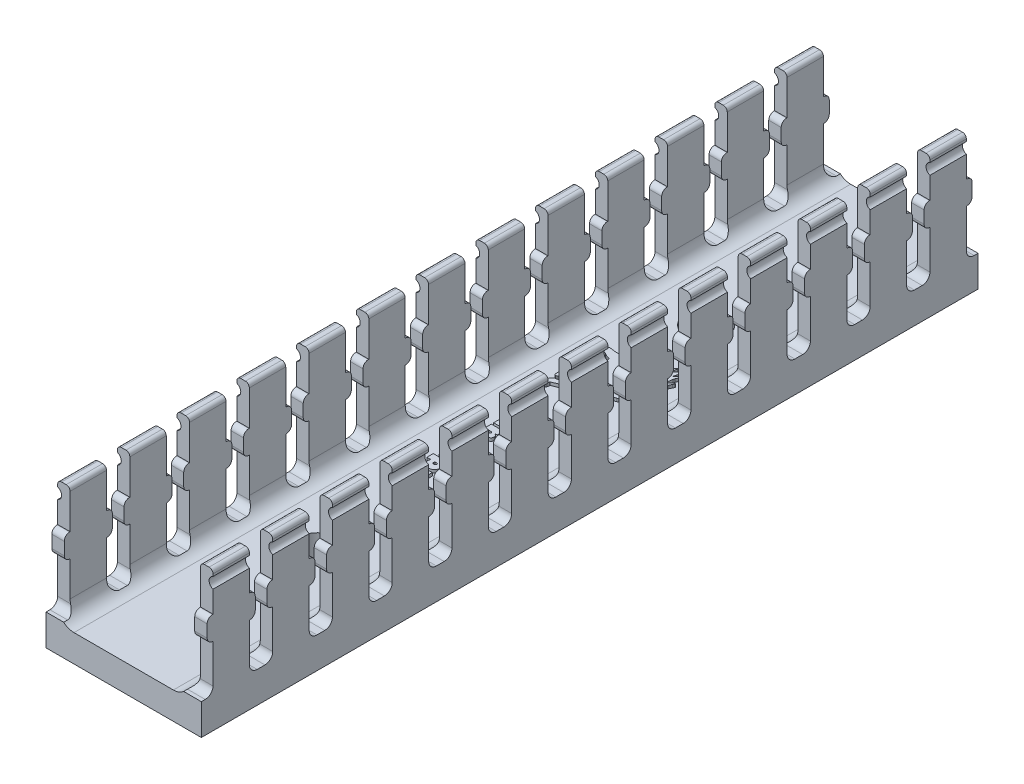
SolidWorks part; units mm, degrees
ref_plane "Front Plane" through (0, 0, 0) normal (0, 0, 1) x (1, 0, 0)
ref_plane "Top Plane" through (0, 0, 0) normal (0, 1, 0) x (1, 0, 0)
ref_plane "Right Plane" through (0, 0, 0) normal (1, 0, 0) x (0, 0, -1)
sketch "Sketch1" plane through (0, 0, 0) normal (0, 0, 1) x (1, 0, 0)
  line L0 (18.9, 18) -> (19.5, 18)
  line L1 (0, 0) -> (20, 0)
  line L2 (0, 0) -> (0, 15.7929)
  line L3 (0.5, 18) -> (1.1, 18)
  line L4 (20, 0) -> (20, 15.7929)
  line L6 (1.6, 17.5) -> (1.6, 5.5)
  line L7 (3.6, 3.5) -> (16.4, 3.5)
  line L8 (18.4, 17.5) -> (18.4, 5.5)
  line L9 (-0.25, 16.5) -> (20.25, 16.5) construction
  line L10 (0, 17.2071) -> (0, 17.5)
  line L11 (20, 17.2071) -> (20, 17.5)
  arc A0 (20, 17.2071) -> (20, 15.7929) centre (20.25, 16.5) ccw
  arc A1 (0, 15.7929) -> (0, 17.2071) centre (-0.25, 16.5) ccw
  arc A2 (1.6, 17.5) -> (1.1, 18) centre (1.1, 17.5) ccw
  arc A3 (18.4, 17.5) -> (18.9, 18) centre (18.9, 17.5) cw
  arc A4 (20, 17.5) -> (19.5, 18) centre (19.5, 17.5) ccw
  arc A5 (0.5, 18) -> (0, 17.5) centre (0.5, 17.5) ccw
  arc A6 (18.4, 5.5) -> (16.4, 3.5) centre (16.4, 5.5) cw
  arc A7 (3.6, 3.5) -> (1.6, 5.5) centre (3.6, 5.5) cw
  point P9 (10, 0)
  point P10 (10, 3.5)
  point P25 (0, 18)
  point P30 (19.5, 16.5)
  point P31 (0.5, 16.5)
  dimension "D5" = 1.5
  dimension "D7" = 0.5
  dimension "D8" = 2
  dimension "D1" = 20
  dimension "D2" = 18
  dimension "D3" = 3.5
  dimension "D4" = 1.6
  dimension "D6" = 1.5
  dimension "D9" = 0.5
  dimension "D10" = 0.5
extrude "Boss-Extrude1" add sketch "Sketch1" along normal blind 100
sketch "Sketch2" plane through (0, 0, 0) normal (-1, 0, 0) x (0, 0, 1)
  line L0 (100, 18) -> (0, 18) construction
  line L1 (-0.5, 4) -> (0.5, 4)
  line L2 (-1.5, 5) -> (-1.5, 10)
  line L3 (-1.5, 18) -> (1.5, 18)
  line L4 (1.5, 5) -> (1.5, 10)
  line L5 (1.45, 10) -> (1.5, 10)
  line L6 (0, 15.7929) -> (0, 0) construction
  line L7 (-1.5, 13) -> (-1.5, 18)
  line L12 (1.5, 13) -> (1.5, 18)
  line L15 (-1.5, 13) -> (-1.45, 13)
  line L17 (-0.75, 12.3) -> (-0.75, 10.7)
  line L19 (0.75, 12.3) -> (0.75, 10.7)
  line L21 (-0.75, 11.5) -> (0.75, 11.5) construction
  line L22 (-1.45, 10) -> (-1.5, 10)
  line L23 (1.45, 13) -> (1.5, 13)
  line L24 (7.1923, 4) -> (8.1923, 4)
  line L37 (100, 0) -> (0, 0) construction
  line L206 (6.1923, 5) -> (6.1923, 10)
  line L246 (6.1923, 18) -> (9.1923, 18)
  line L272 (9.1923, 5) -> (9.1923, 10)
  line L281 (9.1423, 10) -> (9.1923, 10)
  line L294 (6.1923, 13) -> (6.1923, 18)
  line L307 (9.1923, 13) -> (9.1923, 18)
  line L320 (6.1923, 13) -> (6.2423, 13)
  line L333 (6.9423, 12.3) -> (6.9423, 10.7)
  line L346 (8.4423, 12.3) -> (8.4423, 10.7)
  line L359 (6.2423, 10) -> (6.1923, 10)
  line L372 (9.1423, 13) -> (9.1923, 13)
  line L385 (6.9423, 11.5) -> (8.4423, 11.5) construction
  line L398 (14.8846, 4) -> (15.8846, 4)
  line L411 (13.8846, 5) -> (13.8846, 10)
  line L413 (13.8846, 18) -> (16.8846, 18)
  line L414 (16.8846, 5) -> (16.8846, 10)
  line L415 (16.8346, 10) -> (16.8846, 10)
  line L416 (13.8846, 13) -> (13.8846, 18)
  line L417 (16.8846, 13) -> (16.8846, 18)
  line L418 (13.8846, 13) -> (13.9346, 13)
  line L419 (14.6346, 12.3) -> (14.6346, 10.7)
  line L420 (16.1346, 12.3) -> (16.1346, 10.7)
  line L421 (13.9346, 10) -> (13.8846, 10)
  line L422 (16.8346, 13) -> (16.8846, 13)
  line L423 (14.6346, 11.5) -> (16.1346, 11.5) construction
  line L424 (22.5769, 4) -> (23.5769, 4)
  line L425 (21.5769, 5) -> (21.5769, 10)
  line L426 (21.5769, 18) -> (24.5769, 18)
  line L427 (24.5769, 5) -> (24.5769, 10)
  line L428 (24.5269, 10) -> (24.5769, 10)
  line L429 (21.5769, 13) -> (21.5769, 18)
  line L430 (24.5769, 13) -> (24.5769, 18)
  line L431 (21.5769, 13) -> (21.6269, 13)
  line L432 (22.3269, 12.3) -> (22.3269, 10.7)
  line L433 (23.8269, 12.3) -> (23.8269, 10.7)
  line L434 (21.6269, 10) -> (21.5769, 10)
  line L435 (24.5269, 13) -> (24.5769, 13)
  line L436 (22.3269, 11.5) -> (23.8269, 11.5) construction
  line L437 (30.2692, 4) -> (31.2692, 4)
  line L438 (29.2692, 5) -> (29.2692, 10)
  line L439 (29.2692, 18) -> (32.2692, 18)
  line L440 (32.2692, 5) -> (32.2692, 10)
  line L441 (32.2192, 10) -> (32.2692, 10)
  line L442 (29.2692, 13) -> (29.2692, 18)
  line L443 (32.2692, 13) -> (32.2692, 18)
  line L444 (29.2692, 13) -> (29.3192, 13)
  line L445 (30.0192, 12.3) -> (30.0192, 10.7)
  line L446 (31.5192, 12.3) -> (31.5192, 10.7)
  line L447 (29.3192, 10) -> (29.2692, 10)
  line L448 (32.2192, 13) -> (32.2692, 13)
  line L449 (30.0192, 11.5) -> (31.5192, 11.5) construction
  line L450 (37.9615, 4) -> (38.9615, 4)
  line L451 (36.9615, 5) -> (36.9615, 10)
  line L452 (36.9615, 18) -> (39.9615, 18)
  line L453 (39.9615, 5) -> (39.9615, 10)
  line L454 (39.9115, 10) -> (39.9615, 10)
  line L455 (36.9615, 13) -> (36.9615, 18)
  line L456 (39.9615, 13) -> (39.9615, 18)
  line L457 (36.9615, 13) -> (37.0115, 13)
  line L458 (37.7115, 12.3) -> (37.7115, 10.7)
  line L459 (39.2115, 12.3) -> (39.2115, 10.7)
  line L460 (37.0115, 10) -> (36.9615, 10)
  line L461 (39.9115, 13) -> (39.9615, 13)
  line L462 (37.7115, 11.5) -> (39.2115, 11.5) construction
  line L463 (45.6538, 4) -> (46.6538, 4)
  line L464 (44.6538, 5) -> (44.6538, 10)
  line L465 (44.6538, 18) -> (47.6538, 18)
  line L466 (47.6538, 5) -> (47.6538, 10)
  line L467 (47.6038, 10) -> (47.6538, 10)
  line L468 (44.6538, 13) -> (44.6538, 18)
  line L469 (47.6538, 13) -> (47.6538, 18)
  line L470 (44.6538, 13) -> (44.7038, 13)
  line L471 (45.4038, 12.3) -> (45.4038, 10.7)
  line L472 (46.9038, 12.3) -> (46.9038, 10.7)
  line L473 (44.7038, 10) -> (44.6538, 10)
  line L474 (47.6038, 13) -> (47.6538, 13)
  line L475 (45.4038, 11.5) -> (46.9038, 11.5) construction
  line L476 (53.3462, 4) -> (54.3462, 4)
  line L477 (52.3462, 5) -> (52.3462, 10)
  line L478 (52.3462, 18) -> (55.3462, 18)
  line L479 (55.3462, 5) -> (55.3462, 10)
  line L480 (55.2962, 10) -> (55.3462, 10)
  line L481 (52.3462, 13) -> (52.3462, 18)
  line L482 (55.3462, 13) -> (55.3462, 18)
  line L483 (52.3462, 13) -> (52.3962, 13)
  line L484 (53.0962, 12.3) -> (53.0962, 10.7)
  line L485 (54.5962, 12.3) -> (54.5962, 10.7)
  line L486 (52.3962, 10) -> (52.3462, 10)
  line L487 (55.2962, 13) -> (55.3462, 13)
  line L488 (53.0962, 11.5) -> (54.5962, 11.5) construction
  line L489 (61.0385, 4) -> (62.0385, 4)
  line L490 (60.0385, 5) -> (60.0385, 10)
  line L491 (60.0385, 18) -> (63.0385, 18)
  line L492 (63.0385, 5) -> (63.0385, 10)
  line L493 (62.9885, 10) -> (63.0385, 10)
  line L494 (60.0385, 13) -> (60.0385, 18)
  line L495 (63.0385, 13) -> (63.0385, 18)
  line L496 (60.0385, 13) -> (60.0885, 13)
  line L497 (60.7885, 12.3) -> (60.7885, 10.7)
  line L498 (62.2885, 12.3) -> (62.2885, 10.7)
  line L499 (60.0885, 10) -> (60.0385, 10)
  line L500 (62.9885, 13) -> (63.0385, 13)
  line L501 (60.7885, 11.5) -> (62.2885, 11.5) construction
  line L502 (68.7308, 4) -> (69.7308, 4)
  line L503 (67.7308, 5) -> (67.7308, 10)
  line L504 (67.7308, 18) -> (70.7308, 18)
  line L505 (70.7308, 5) -> (70.7308, 10)
  line L506 (70.6808, 10) -> (70.7308, 10)
  line L507 (67.7308, 13) -> (67.7308, 18)
  line L508 (70.7308, 13) -> (70.7308, 18)
  line L509 (67.7308, 13) -> (67.7808, 13)
  line L510 (68.4808, 12.3) -> (68.4808, 10.7)
  line L511 (69.9808, 12.3) -> (69.9808, 10.7)
  line L512 (67.7808, 10) -> (67.7308, 10)
  line L513 (70.6808, 13) -> (70.7308, 13)
  line L514 (68.4808, 11.5) -> (69.9808, 11.5) construction
  line L515 (76.4231, 4) -> (77.4231, 4)
  line L516 (75.4231, 5) -> (75.4231, 10)
  line L517 (75.4231, 18) -> (78.4231, 18)
  line L518 (78.4231, 5) -> (78.4231, 10)
  line L519 (78.3731, 10) -> (78.4231, 10)
  line L520 (75.4231, 13) -> (75.4231, 18)
  line L521 (78.4231, 13) -> (78.4231, 18)
  line L522 (75.4231, 13) -> (75.4731, 13)
  line L523 (76.1731, 12.3) -> (76.1731, 10.7)
  line L524 (77.6731, 12.3) -> (77.6731, 10.7)
  line L525 (75.4731, 10) -> (75.4231, 10)
  line L526 (78.3731, 13) -> (78.4231, 13)
  line L527 (76.1731, 11.5) -> (77.6731, 11.5) construction
  line L528 (84.1154, 4) -> (85.1154, 4)
  line L529 (83.1154, 5) -> (83.1154, 10)
  line L530 (83.1154, 18) -> (86.1154, 18)
  line L531 (86.1154, 5) -> (86.1154, 10)
  line L532 (86.0654, 10) -> (86.1154, 10)
  line L533 (83.1154, 13) -> (83.1154, 18)
  line L534 (86.1154, 13) -> (86.1154, 18)
  line L535 (83.1154, 13) -> (83.1654, 13)
  line L536 (83.8654, 12.3) -> (83.8654, 10.7)
  line L537 (85.3654, 12.3) -> (85.3654, 10.7)
  line L538 (83.1654, 10) -> (83.1154, 10)
  line L539 (86.0654, 13) -> (86.1154, 13)
  line L540 (83.8654, 11.5) -> (85.3654, 11.5) construction
  line L541 (91.8077, 4) -> (92.8077, 4)
  line L542 (90.8077, 5) -> (90.8077, 10)
  line L543 (90.8077, 18) -> (93.8077, 18)
  line L544 (93.8077, 5) -> (93.8077, 10)
  line L545 (93.7577, 10) -> (93.8077, 10)
  line L546 (90.8077, 13) -> (90.8077, 18)
  line L547 (93.8077, 13) -> (93.8077, 18)
  line L548 (90.8077, 13) -> (90.8577, 13)
  line L549 (91.5577, 12.3) -> (91.5577, 10.7)
  line L550 (93.0577, 12.3) -> (93.0577, 10.7)
  line L551 (90.8577, 10) -> (90.8077, 10)
  line L552 (93.7577, 13) -> (93.8077, 13)
  line L553 (91.5577, 11.5) -> (93.0577, 11.5) construction
  line L554 (99.5, 4) -> (100.5, 4)
  line L555 (98.5, 5) -> (98.5, 10)
  line L556 (98.5, 18) -> (101.5, 18)
  line L557 (101.5, 5) -> (101.5, 10)
  line L558 (101.45, 10) -> (101.5, 10)
  line L559 (98.5, 13) -> (98.5, 18)
  line L560 (101.5, 13) -> (101.5, 18)
  line L561 (98.5, 13) -> (98.55, 13)
  line L562 (99.25, 12.3) -> (99.25, 10.7)
  line L563 (100.75, 12.3) -> (100.75, 10.7)
  line L564 (98.55, 10) -> (98.5, 10)
  line L565 (101.45, 13) -> (101.5, 13)
  line L566 (99.25, 11.5) -> (100.75, 11.5) construction
  line L567 (100, 15.7929) -> (100, 0) construction
  arc A0 (-0.5, 4) -> (-1.5, 5) centre (-0.5, 5) cw
  arc A1 (0.5, 4) -> (1.5, 5) centre (0.5, 5) ccw
  arc A2 (-1.45, 13) -> (-0.75, 12.3) centre (-1.45, 12.3) cw
  arc A3 (-1.45, 10) -> (-0.75, 10.7) centre (-1.45, 10.7) ccw
  arc A4 (1.45, 10) -> (0.75, 10.7) centre (1.45, 10.7) cw
  arc A5 (1.45, 13) -> (0.75, 12.3) centre (1.45, 12.3) ccw
  arc A192 (7.1923, 4) -> (6.1923, 5) centre (7.1923, 5) cw
  arc A193 (8.1923, 4) -> (9.1923, 5) centre (8.1923, 5) ccw
  arc A194 (6.2423, 13) -> (6.9423, 12.3) centre (6.2423, 12.3) cw
  arc A195 (6.2423, 10) -> (6.9423, 10.7) centre (6.2423, 10.7) ccw
  arc A196 (9.1423, 10) -> (8.4423, 10.7) centre (9.1423, 10.7) cw
  arc A197 (9.1423, 13) -> (8.4423, 12.3) centre (9.1423, 12.3) ccw
  arc A198 (14.8846, 4) -> (13.8846, 5) centre (14.8846, 5) cw
  arc A199 (15.8846, 4) -> (16.8846, 5) centre (15.8846, 5) ccw
  arc A200 (13.9346, 13) -> (14.6346, 12.3) centre (13.9346, 12.3) cw
  arc A201 (13.9346, 10) -> (14.6346, 10.7) centre (13.9346, 10.7) ccw
  arc A202 (16.8346, 10) -> (16.1346, 10.7) centre (16.8346, 10.7) cw
  arc A203 (16.8346, 13) -> (16.1346, 12.3) centre (16.8346, 12.3) ccw
  arc A204 (22.5769, 4) -> (21.5769, 5) centre (22.5769, 5) cw
  arc A205 (23.5769, 4) -> (24.5769, 5) centre (23.5769, 5) ccw
  arc A206 (21.6269, 13) -> (22.3269, 12.3) centre (21.6269, 12.3) cw
  arc A207 (21.6269, 10) -> (22.3269, 10.7) centre (21.6269, 10.7) ccw
  arc A208 (24.5269, 10) -> (23.8269, 10.7) centre (24.5269, 10.7) cw
  arc A209 (24.5269, 13) -> (23.8269, 12.3) centre (24.5269, 12.3) ccw
  arc A210 (30.2692, 4) -> (29.2692, 5) centre (30.2692, 5) cw
  arc A211 (31.2692, 4) -> (32.2692, 5) centre (31.2692, 5) ccw
  arc A212 (29.3192, 13) -> (30.0192, 12.3) centre (29.3192, 12.3) cw
  arc A213 (29.3192, 10) -> (30.0192, 10.7) centre (29.3192, 10.7) ccw
  arc A214 (32.2192, 10) -> (31.5192, 10.7) centre (32.2192, 10.7) cw
  arc A215 (32.2192, 13) -> (31.5192, 12.3) centre (32.2192, 12.3) ccw
  arc A216 (37.9615, 4) -> (36.9615, 5) centre (37.9615, 5) cw
  arc A217 (38.9615, 4) -> (39.9615, 5) centre (38.9615, 5) ccw
  arc A218 (37.0115, 13) -> (37.7115, 12.3) centre (37.0115, 12.3) cw
  arc A219 (37.0115, 10) -> (37.7115, 10.7) centre (37.0115, 10.7) ccw
  arc A220 (39.9115, 10) -> (39.2115, 10.7) centre (39.9115, 10.7) cw
  arc A221 (39.9115, 13) -> (39.2115, 12.3) centre (39.9115, 12.3) ccw
  arc A222 (45.6538, 4) -> (44.6538, 5) centre (45.6538, 5) cw
  arc A223 (46.6538, 4) -> (47.6538, 5) centre (46.6538, 5) ccw
  arc A224 (44.7038, 13) -> (45.4038, 12.3) centre (44.7038, 12.3) cw
  arc A225 (44.7038, 10) -> (45.4038, 10.7) centre (44.7038, 10.7) ccw
  arc A226 (47.6038, 10) -> (46.9038, 10.7) centre (47.6038, 10.7) cw
  arc A227 (47.6038, 13) -> (46.9038, 12.3) centre (47.6038, 12.3) ccw
  arc A228 (53.3462, 4) -> (52.3462, 5) centre (53.3462, 5) cw
  arc A229 (54.3462, 4) -> (55.3462, 5) centre (54.3462, 5) ccw
  arc A230 (52.3962, 13) -> (53.0962, 12.3) centre (52.3962, 12.3) cw
  arc A231 (52.3962, 10) -> (53.0962, 10.7) centre (52.3962, 10.7) ccw
  arc A232 (55.2962, 10) -> (54.5962, 10.7) centre (55.2962, 10.7) cw
  arc A233 (55.2962, 13) -> (54.5962, 12.3) centre (55.2962, 12.3) ccw
  arc A234 (61.0385, 4) -> (60.0385, 5) centre (61.0385, 5) cw
  arc A235 (62.0385, 4) -> (63.0385, 5) centre (62.0385, 5) ccw
  arc A236 (60.0885, 13) -> (60.7885, 12.3) centre (60.0885, 12.3) cw
  arc A237 (60.0885, 10) -> (60.7885, 10.7) centre (60.0885, 10.7) ccw
  arc A238 (62.9885, 10) -> (62.2885, 10.7) centre (62.9885, 10.7) cw
  arc A239 (62.9885, 13) -> (62.2885, 12.3) centre (62.9885, 12.3) ccw
  arc A240 (68.7308, 4) -> (67.7308, 5) centre (68.7308, 5) cw
  arc A241 (69.7308, 4) -> (70.7308, 5) centre (69.7308, 5) ccw
  arc A242 (67.7808, 13) -> (68.4808, 12.3) centre (67.7808, 12.3) cw
  arc A243 (67.7808, 10) -> (68.4808, 10.7) centre (67.7808, 10.7) ccw
  arc A244 (70.6808, 10) -> (69.9808, 10.7) centre (70.6808, 10.7) cw
  arc A245 (70.6808, 13) -> (69.9808, 12.3) centre (70.6808, 12.3) ccw
  arc A246 (76.4231, 4) -> (75.4231, 5) centre (76.4231, 5) cw
  arc A247 (77.4231, 4) -> (78.4231, 5) centre (77.4231, 5) ccw
  arc A248 (75.4731, 13) -> (76.1731, 12.3) centre (75.4731, 12.3) cw
  arc A249 (75.4731, 10) -> (76.1731, 10.7) centre (75.4731, 10.7) ccw
  arc A250 (78.3731, 10) -> (77.6731, 10.7) centre (78.3731, 10.7) cw
  arc A251 (78.3731, 13) -> (77.6731, 12.3) centre (78.3731, 12.3) ccw
  arc A252 (84.1154, 4) -> (83.1154, 5) centre (84.1154, 5) cw
  arc A253 (85.1154, 4) -> (86.1154, 5) centre (85.1154, 5) ccw
  arc A254 (83.1654, 13) -> (83.8654, 12.3) centre (83.1654, 12.3) cw
  arc A255 (83.1654, 10) -> (83.8654, 10.7) centre (83.1654, 10.7) ccw
  arc A256 (86.0654, 10) -> (85.3654, 10.7) centre (86.0654, 10.7) cw
  arc A257 (86.0654, 13) -> (85.3654, 12.3) centre (86.0654, 12.3) ccw
  arc A258 (91.8077, 4) -> (90.8077, 5) centre (91.8077, 5) cw
  arc A259 (92.8077, 4) -> (93.8077, 5) centre (92.8077, 5) ccw
  arc A260 (90.8577, 13) -> (91.5577, 12.3) centre (90.8577, 12.3) cw
  arc A261 (90.8577, 10) -> (91.5577, 10.7) centre (90.8577, 10.7) ccw
  arc A262 (93.7577, 10) -> (93.0577, 10.7) centre (93.7577, 10.7) cw
  arc A263 (93.7577, 13) -> (93.0577, 12.3) centre (93.7577, 12.3) ccw
  arc A264 (99.5, 4) -> (98.5, 5) centre (99.5, 5) cw
  arc A265 (100.5, 4) -> (101.5, 5) centre (100.5, 5) ccw
  arc A266 (98.55, 13) -> (99.25, 12.3) centre (98.55, 12.3) cw
  arc A267 (98.55, 10) -> (99.25, 10.7) centre (98.55, 10.7) ccw
  arc A268 (101.45, 10) -> (100.75, 10.7) centre (101.45, 10.7) cw
  arc A269 (101.45, 13) -> (100.75, 12.3) centre (101.45, 12.3) ccw
  point P18 (0, 11.5)
  point P19 (0, 18)
  point P26 (0.75, 10)
  point P29 (0.75, 13)
  point P31 (0, 4)
  point P35 (100, 4)
  dimension "D4" = 1
  dimension "D7" = 14
  dimension "D5" = 0.7
  dimension "D1" = 3
  dimension "D2" = 1.5
  dimension "D3" = 4
  dimension "D6" = 3
extrude "Cut-Extrude1" cut sketch "Sketch2" against normal through all
sketch "Sketch3" plane through (0, 3.5, 0) normal (0, 1, 0) x (1, 0, 0)
  line L0 (10, 0) -> (10, -100) construction
  line L1 (16.4, 0) -> (3.6, 0) construction
  line L2 (16.4, -100) -> (3.6, -100) construction
  circle A0 centre (10, -25) radius 2.6
  circle A3 centre (10, -75) radius 2.6
  circle A4 centre (10, -58.3333) radius 2.6 [skipped]
  circle A5 centre (10, -41.6667) radius 2.6 [skipped]
  dimension "D2" = 5.2
  dimension "D4" = 25
  dimension "D1" = 25
  dimension "D3" = 4
extrude "Cut-Extrude2" cut sketch "Sketch3" against normal through all
sketch "Sketch5" plane through (2.8658, 3.5, -37.4804) normal (0, 1, 0) x (1, 0, 0)
  line L4 (12.1147, -71.3896) -> (12.0797, -71.4016)
  line L5 (12.0797, -71.4016) -> (12.0456, -71.4149)
  line L6 (12.0456, -71.4149) -> (12.0122, -71.4295)
  line L7 (12.0122, -71.4295) -> (11.9795, -71.4453)
  line L8 (11.9795, -71.4453) -> (11.9476, -71.4622)
  line L9 (11.9476, -71.4622) -> (11.9163, -71.4802)
  line L10 (11.9163, -71.4802) -> (11.8857, -71.4992)
  line L11 (11.8857, -71.4992) -> (11.8558, -71.5192)
  line L12 (11.8558, -71.5192) -> (11.8264, -71.5401)
  line L13 (11.8264, -71.5401) -> (11.7976, -71.5619)
  line L14 (11.7976, -71.5619) -> (11.7693, -71.5844)
  line L15 (11.7693, -71.5844) -> (11.7415, -71.6076)
  line L16 (11.7415, -71.6076) -> (11.7142, -71.6316)
  line L17 (11.7142, -71.6316) -> (11.6608, -71.6812)
  line L18 (11.6608, -71.6812) -> (11.5835, -71.7592)
  line L19 (11.5835, -71.7592) -> (11.316, -72.0573)
  line L20 (11.316, -72.0573) -> (11.3221, -71.9943)
  line L21 (11.3221, -71.9943) -> (11.457, -71.1518)
  line L22 (11.457, -71.1518) -> (11.4618, -71.1201)
  line L23 (11.4618, -71.1201) -> (11.4675, -71.0887)
  line L24 (11.4675, -71.0887) -> (11.4741, -71.0575)
  line L25 (11.4741, -71.0575) -> (11.4814, -71.0266)
  line L26 (11.4814, -71.0266) -> (11.4983, -70.9655)
  line L27 (11.4983, -70.9655) -> (11.5177, -70.9053)
  line L28 (11.5177, -70.9053) -> (11.5508, -70.8162)
  line L29 (11.5508, -70.8162) -> (11.7296, -70.4087)
  line L30 (11.7296, -70.4087) -> (11.7755, -70.2905)
  line L31 (11.7755, -70.2905) -> (11.7451, -70.2959)
  line L32 (11.7451, -70.2959) -> (11.7156, -70.3028)
  line L33 (11.7156, -70.3028) -> (11.6867, -70.3111)
  line L34 (11.6867, -70.3111) -> (11.6586, -70.3207)
  line L35 (11.6586, -70.3207) -> (11.6312, -70.3317)
  line L36 (11.6312, -70.3317) -> (11.6044, -70.3439)
  line L37 (11.6044, -70.3439) -> (11.5782, -70.3572)
  line L38 (11.5782, -70.3572) -> (11.5527, -70.3716)
  line L39 (11.5527, -70.3716) -> (11.5276, -70.387)
  line L40 (11.5276, -70.387) -> (11.5031, -70.4034)
  line L41 (11.5031, -70.4034) -> (11.4791, -70.4206)
  line L42 (11.4791, -70.4206) -> (11.4555, -70.4386)
  line L43 (11.4555, -70.4386) -> (11.4096, -70.4766)
  line L44 (11.4096, -70.4766) -> (11.3651, -70.5169)
  line L45 (11.3651, -70.5169) -> (11.2792, -70.6019)
  line L46 (11.2792, -70.6019) -> (11.0915, -70.7939)
  line L47 (11.0915, -70.7939) -> (11.1111, -70.7092)
  line L48 (11.1111, -70.7092) -> (11.1556, -70.5412)
  line L49 (11.1556, -70.5412) -> (11.2064, -70.3751)
  line L50 (11.2064, -70.3751) -> (11.2927, -70.1292)
  line L51 (11.2927, -70.1292) -> (11.5092, -69.6077)
  line L52 (11.5092, -69.6077) -> (11.4913, -69.6096)
  line L53 (11.4913, -69.6096) -> (11.4561, -69.6154)
  line L54 (11.4561, -69.6154) -> (11.4217, -69.6235)
  line L55 (11.4217, -69.6235) -> (11.3879, -69.6339)
  line L56 (11.3879, -69.6339) -> (11.3387, -69.6533)
  line L57 (11.3387, -69.6533) -> (11.2911, -69.6768)
  line L58 (11.2911, -69.6768) -> (11.2153, -69.7233)
  line L59 (11.2153, -69.7233) -> (11.063, -69.8456)
  line L60 (11.063, -69.8456) -> (10.6773, -70.2688)
  line L61 (10.6773, -70.2688) -> (10.5495, -70.4457)
  line L62 (10.5495, -70.4457) -> (10.3815, -70.6663)
  line L63 (10.3815, -70.6663) -> (10.5311, -69.9815)
  line L64 (10.5311, -69.9815) -> (10.6096, -69.5705)
  line L65 (10.6096, -69.5705) -> (10.5718, -69.5918)
  line L66 (10.5718, -69.5918) -> (10.5357, -69.6146)
  line L67 (10.5357, -69.6146) -> (10.5011, -69.639)
  line L68 (10.5011, -69.639) -> (10.468, -69.6649)
  line L69 (10.468, -69.6649) -> (10.4364, -69.6921)
  line L70 (10.4364, -69.6921) -> (10.4061, -69.7206)
  line L71 (10.4061, -69.7206) -> (10.3771, -69.7503)
  line L72 (10.3771, -69.7503) -> (10.3493, -69.7812)
  line L73 (10.3493, -69.7812) -> (10.3226, -69.813)
  line L74 (10.3226, -69.813) -> (10.297, -69.8459)
  line L75 (10.297, -69.8459) -> (10.2723, -69.8796)
  line L76 (10.2723, -69.8796) -> (10.2485, -69.9141)
  line L77 (10.2485, -69.9141) -> (10.2256, -69.9494)
  line L78 (10.2256, -69.9494) -> (10.2033, -69.9853)
  line L79 (10.2033, -69.9853) -> (10.1607, -70.0587)
  line L80 (10.1607, -70.0587) -> (10.1004, -70.1715)
  line L81 (10.1004, -70.1715) -> (9.9459, -70.4732)
  line L82 (9.9459, -70.4732) -> (9.9053, -70.5453)
  line L83 (9.9053, -70.5453) -> (9.8688, -70.2365)
  line L84 (9.8688, -70.2365) -> (9.8546, -70.2454)
  line L85 (9.8546, -70.2454) -> (9.828, -70.2647)
  line L86 (9.828, -70.2647) -> (9.8034, -70.2859)
  line L87 (9.8034, -70.2859) -> (9.7806, -70.3089)
  line L88 (9.7806, -70.3089) -> (9.7597, -70.3334)
  line L89 (9.7597, -70.3334) -> (9.7312, -70.3728)
  line L90 (9.7312, -70.3728) -> (9.6982, -70.4292)
  line L91 (9.6982, -70.4292) -> (9.6174, -70.6257)
  line L92 (9.6174, -70.6257) -> (9.5985, -70.6861)
  line L93 (9.5985, -70.6861) -> (9.4099, -71.5185)
  line L94 (9.4099, -71.5185) -> (9.2974, -71.3478)
  line L95 (9.2974, -71.3478) -> (9.2818, -71.4368)
  line L96 (9.2818, -71.4368) -> (9.21, -71.885)
  line L97 (9.21, -71.885) -> (9.1891, -71.9731)
  line L98 (9.1891, -71.9731) -> (9.1725, -72.0312)
  line L99 (9.1725, -72.0312) -> (9.1534, -72.0886)
  line L100 (9.1534, -72.0886) -> (9.1316, -72.1453)
  line L101 (9.1316, -72.1453) -> (9.1195, -72.1733)
  line L102 (9.1195, -72.1733) -> (9.1066, -72.2011)
  line L103 (9.1066, -72.2011) -> (9.0349, -72.1307)
  line L104 (9.0349, -72.1307) -> (8.9161, -72.2495)
  line L105 (8.9161, -72.2495) -> (8.8729, -72.3141)
  line L106 (8.8729, -72.3141) -> (8.8547, -72.3549)
  line L107 (8.8547, -72.3549) -> (8.845, -72.3876)
  line L108 (8.845, -72.3876) -> (8.8399, -72.4089)
  line L109 (8.8399, -72.4089) -> (8.8278, -72.4729)
  line L110 (8.8278, -72.4729) -> (8.8155, -72.5805)
  line L111 (8.8155, -72.5805) -> (8.7946, -73.0142)
  line L112 (8.7946, -73.0142) -> (8.6906, -72.9558)
  line L113 (8.6906, -72.9558) -> (8.6736, -72.9994)
  line L114 (8.6736, -72.9994) -> (8.6448, -73.088)
  line L115 (8.6448, -73.088) -> (8.6226, -73.1782)
  line L116 (8.6226, -73.1782) -> (8.6032, -73.2928)
  line L117 (8.6032, -73.2928) -> (8.5914, -73.4319)
  line L118 (8.5914, -73.4319) -> (8.5924, -73.6182)
  line L119 (8.5924, -73.6182) -> (8.4936, -73.6392)
  line L120 (8.4936, -73.6392) -> (8.4701, -73.6544)
  line L121 (8.4701, -73.6544) -> (8.4591, -73.6677)
  line L122 (8.4591, -73.6677) -> (8.4535, -73.6786)
  line L123 (8.4535, -73.6786) -> (8.4493, -73.6914)
  line L124 (8.4493, -73.6914) -> (8.4459, -73.707)
  line L125 (8.4459, -73.707) -> (8.4414, -73.7383)
  line L126 (8.4414, -73.7383) -> (8.4398, -73.7695)
  line L127 (8.4398, -73.7695) -> (8.4407, -73.8005)
  line L128 (8.4407, -73.8005) -> (8.444, -73.8314)
  line L129 (8.444, -73.8314) -> (8.4564, -73.8927)
  line L130 (8.4564, -73.8927) -> (8.5426, -74.1299)
  line L131 (8.5426, -74.1299) -> (8.3866, -74.0719)
  line L132 (8.3866, -74.0719) -> (8.3921, -74.6914)
  line L133 (8.3921, -74.6914) -> (8.3903, -74.715)
  line L134 (8.3903, -74.715) -> (8.3875, -74.7384)
  line L135 (8.3875, -74.7384) -> (8.3838, -74.7615)
  line L136 (8.3838, -74.7615) -> (8.3792, -74.7843)
  line L137 (8.3792, -74.7843) -> (8.3737, -74.8069)
  line L138 (8.3737, -74.8069) -> (8.3674, -74.8291)
  line L139 (8.3674, -74.8291) -> (8.3603, -74.8511)
  line L140 (8.3603, -74.8511) -> (8.3524, -74.8727)
  line L141 (8.3524, -74.8727) -> (8.3437, -74.8941)
  line L142 (8.3437, -74.8941) -> (8.3343, -74.9151)
  line L143 (8.3343, -74.9151) -> (8.3133, -74.9562)
  line L144 (8.3133, -74.9562) -> (8.2898, -74.996)
  line L145 (8.2898, -74.996) -> (8.2639, -75.0345)
  line L146 (8.2639, -75.0345) -> (8.2358, -75.0716)
  line L147 (8.2358, -75.0716) -> (8.2058, -75.1073)
  line L148 (8.2058, -75.1073) -> (8.1576, -75.1582)
  line L149 (8.1576, -75.1582) -> (8.1063, -75.2056)
  line L150 (8.1063, -75.2056) -> (8.0527, -75.2495)
  line L151 (8.0527, -75.2495) -> (8.0056, -75.0091)
  line L152 (8.0056, -75.0091) -> (8.0114, -74.9722)
  line L153 (8.0114, -74.9722) -> (8.0183, -74.9355)
  line L154 (8.0183, -74.9355) -> (8.026, -74.8991)
  line L155 (8.026, -74.8991) -> (8.0346, -74.8629)
  line L156 (8.0346, -74.8629) -> (8.054, -74.7912)
  line L157 (8.054, -74.7912) -> (8.0876, -74.6847)
  line L158 (8.0876, -74.6847) -> (8.2231, -74.2977)
  line L159 (8.2231, -74.2977) -> (8.2444, -74.2264)
  line L160 (8.2444, -74.2264) -> (8.263, -74.1545)
  line L161 (8.263, -74.1545) -> (8.2711, -74.1183)
  line L162 (8.2711, -74.1183) -> (8.2784, -74.0818)
  line L163 (8.2784, -74.0818) -> (8.2846, -74.0451)
  line L164 (8.2846, -74.0451) -> (8.2899, -74.008)
  line L165 (8.2899, -74.008) -> (8.294, -73.9707)
  line L166 (8.294, -73.9707) -> (8.2973, -73.9399)
  line L167 (8.2973, -73.9399) -> (8.3022, -73.8779)
  line L168 (8.3022, -73.8779) -> (8.3047, -73.8157)
  line L169 (8.3047, -73.8157) -> (8.3047, -73.7535)
  line L170 (8.3047, -73.7535) -> (8.3024, -73.6913)
  line L171 (8.3024, -73.6913) -> (8.2975, -73.6293)
  line L172 (8.2975, -73.6293) -> (8.2902, -73.5675)
  line L173 (8.2902, -73.5675) -> (8.2803, -73.5061)
  line L174 (8.2803, -73.5061) -> (8.2678, -73.4453)
  line L175 (8.2678, -73.4453) -> (8.2527, -73.385)
  line L176 (8.2527, -73.385) -> (8.235, -73.3255)
  line L177 (8.235, -73.3255) -> (8.2146, -73.2668)
  line L178 (8.2146, -73.2668) -> (8.1915, -73.2091)
  line L179 (8.1915, -73.2091) -> (8.1657, -73.1524)
  line L180 (8.1657, -73.1524) -> (8.1371, -73.097)
  line L181 (8.1371, -73.097) -> (8.0627, -72.9622)
  line L182 (8.0627, -72.9622) -> (8.0106, -72.8733)
  line L183 (8.0106, -72.8733) -> (7.9563, -72.7856)
  line L184 (7.9563, -72.7856) -> (7.8999, -72.6992)
  line L185 (7.8999, -72.6992) -> (7.8412, -72.6143)
  line L186 (7.8412, -72.6143) -> (7.7801, -72.5313)
  line L187 (7.7801, -72.5313) -> (7.7486, -72.4905)
  line L188 (7.7486, -72.4905) -> (7.7164, -72.4503)
  line L189 (7.7164, -72.4503) -> (7.6837, -72.4106)
  line L190 (7.6837, -72.4106) -> (7.6502, -72.3715)
  line L191 (7.6502, -72.3715) -> (7.6161, -72.333)
  line L192 (7.6161, -72.333) -> (7.5813, -72.2951)
  line L193 (7.5813, -72.2951) -> (7.5458, -72.258)
  line L194 (7.5458, -72.258) -> (7.5096, -72.2215)
  line L195 (7.5096, -72.2215) -> (7.4727, -72.1858)
  line L196 (7.4727, -72.1858) -> (7.4351, -72.1508)
  line L197 (7.4351, -72.1508) -> (7.3967, -72.1167)
  line L198 (7.3967, -72.1167) -> (7.3575, -72.0833)
  line L199 (7.3575, -72.0833) -> (7.3176, -72.0508)
  line L200 (7.3176, -72.0508) -> (7.2769, -72.0192)
  line L201 (7.2769, -72.0192) -> (7.2354, -71.9884)
  line L202 (7.2354, -71.9884) -> (7.1931, -71.9586)
  line L203 (7.1931, -71.9586) -> (6.622, -71.5566)
  line L204 (6.622, -71.5566) -> (6.5859, -71.5335)
  line L205 (6.5859, -71.5335) -> (6.1352, -71.1744)
  line L206 (6.1352, -71.1744) -> (6.0321, -71.091)
  line L207 (6.0321, -71.091) -> (5.9318, -71.0043)
  line L208 (5.9318, -71.0043) -> (5.8023, -70.8841)
  line L209 (5.8023, -70.8841) -> (5.6776, -70.7589)
  line L210 (5.6776, -70.7589) -> (5.5574, -70.6293)
  line L211 (5.5574, -70.6293) -> (5.4134, -70.4616)
  line L212 (5.4134, -70.4616) -> (5.2495, -70.2533)
  line L213 (5.2495, -70.2533) -> (5.167, -70.1347)
  line L214 (5.167, -70.1347) -> (5.1388, -70.0745)
  line L215 (5.1388, -70.0745) -> (5.1303, -70.0376)
  line L216 (5.1303, -70.0376) -> (5.1288, -70.0083)
  line L217 (5.1288, -70.0083) -> (5.1283, -69.9945)
  line L218 (5.1283, -69.9945) -> (5.1288, -69.9809)
  line L219 (5.1288, -69.9809) -> (5.1301, -69.9674)
  line L220 (5.1301, -69.9674) -> (5.1349, -69.9407)
  line L221 (5.1349, -69.9407) -> (5.1422, -69.9144)
  line L222 (5.1422, -69.9144) -> (5.1977, -69.7724)
  line L223 (5.1977, -69.7724) -> (5.2085, -69.7333)
  line L224 (5.2085, -69.7333) -> (5.2125, -69.7069)
  line L225 (5.2125, -69.7069) -> (5.2133, -69.6935)
  line L226 (5.2133, -69.6935) -> (5.2133, -69.68)
  line L227 (5.2133, -69.68) -> (5.2122, -69.6664)
  line L228 (5.2122, -69.6664) -> (5.2101, -69.6526)
  line L229 (5.2101, -69.6526) -> (5.2069, -69.6387)
  line L230 (5.2069, -69.6387) -> (5.2024, -69.6246)
  line L231 (5.2024, -69.6246) -> (5.0443, -69.165)
  line L232 (5.0443, -69.165) -> (4.9577, -69.1852)
  line L233 (4.9577, -69.1852) -> (4.8328, -68.8633)
  line L234 (4.8328, -68.8633) -> (4.7596, -68.9567)
  line L235 (4.7596, -68.9567) -> (4.5862, -68.7642)
  line L236 (4.5862, -68.7642) -> (4.5232, -68.8529)
  line L237 (4.5232, -68.8529) -> (4.48, -68.8345)
  line L238 (4.48, -68.8345) -> (4.3018, -68.7798)
  line L239 (4.3018, -68.7798) -> (4.1789, -68.7634)
  line L240 (4.1789, -68.7634) -> (4.085, -68.7636)
  line L241 (4.085, -68.7636) -> (4.0805, -68.8982)
  line L242 (4.0805, -68.8982) -> (3.8868, -69.0851)
  line L243 (3.8868, -69.0851) -> (3.9578, -69.1179)
  line L244 (3.9578, -69.1179) -> (4.0886, -69.1799)
  line L245 (4.0886, -69.1799) -> (4.1196, -69.2023)
  line L246 (4.1196, -69.2023) -> (4.1382, -69.2194)
  line L247 (4.1382, -69.2194) -> (4.155, -69.2387)
  line L248 (4.155, -69.2387) -> (4.1625, -69.2492)
  line L249 (4.1625, -69.2492) -> (4.1695, -69.2603)
  line L250 (4.1695, -69.2603) -> (4.1759, -69.2722)
  line L251 (4.1759, -69.2722) -> (4.1816, -69.2847)
  line L252 (4.1816, -69.2847) -> (4.1866, -69.298)
  line L253 (4.1866, -69.298) -> (4.0551, -69.3268)
  line L254 (4.0551, -69.3268) -> (4.0642, -69.3695)
  line L255 (4.0642, -69.3695) -> (4.0962, -69.465)
  line L256 (4.0962, -69.465) -> (4.2335, -69.7015)
  line L257 (4.2335, -69.7015) -> (4.1951, -69.8156)
  line L258 (4.1951, -69.8156) -> (4.1942, -69.8788)
  line L259 (4.1942, -69.8788) -> (4.2051, -69.9025)
  line L260 (4.2051, -69.9025) -> (4.2377, -69.9583)
  line L261 (4.2377, -69.9583) -> (4.4325, -70.1651)
  line L262 (4.4325, -70.1651) -> (4.446, -70.1774)
  line L263 (4.446, -70.1774) -> (4.4843, -70.216)
  line L264 (4.4843, -70.216) -> (4.5417, -70.2854)
  line L265 (4.5417, -70.2854) -> (4.7492, -70.5817)
  line L266 (4.7492, -70.5817) -> (4.7864, -70.6316)
  line L267 (4.7864, -70.6316) -> (4.8243, -70.6808)
  line L268 (4.8243, -70.6808) -> (4.863, -70.7293)
  line L269 (4.863, -70.7293) -> (4.9024, -70.7772)
  line L270 (4.9024, -70.7772) -> (4.9425, -70.8245)
  line L271 (4.9425, -70.8245) -> (4.9833, -70.8711)
  line L272 (4.9833, -70.8711) -> (5.0247, -70.9172)
  line L273 (5.0247, -70.9172) -> (5.0667, -70.9626)
  line L274 (5.0667, -70.9626) -> (5.1093, -71.0076)
  line L275 (5.1093, -71.0076) -> (5.1961, -71.0959)
  line L276 (5.1961, -71.0959) -> (5.285, -71.1822)
  line L277 (5.285, -71.1822) -> (5.3757, -71.2668)
  line L278 (5.3757, -71.2668) -> (5.4679, -71.3497)
  line L279 (5.4679, -71.3497) -> (5.6088, -71.4714)
  line L280 (5.6088, -71.4714) -> (6.0428, -71.822)
  line L281 (6.0428, -71.822) -> (6.0659, -71.8442)
  line L282 (6.0659, -71.8442) -> (6.1133, -71.8869)
  line L283 (6.1133, -71.8869) -> (6.1868, -71.9479)
  line L284 (6.1868, -71.9479) -> (6.34, -72.0615)
  line L285 (6.34, -72.0615) -> (6.7021, -72.3212)
  line L286 (6.7021, -72.3212) -> (6.7754, -72.3826)
  line L287 (6.7754, -72.3826) -> (6.512, -72.3981)
  line L288 (6.512, -72.3981) -> (6.4504, -72.3906)
  line L289 (6.4504, -72.3906) -> (6.4141, -72.3811)
  line L290 (6.4141, -72.3811) -> (6.3352, -72.3212)
  line L291 (6.3352, -72.3212) -> (5.801, -71.8776)
  line L292 (5.801, -71.8776) -> (5.6679, -71.7798)
  line L293 (5.6679, -71.7798) -> (5.6417, -71.7633)
  line L294 (5.6417, -71.7633) -> (5.6152, -71.7487)
  line L295 (5.6152, -71.7487) -> (5.5883, -71.7358)
  line L296 (5.5883, -71.7358) -> (5.561, -71.7245)
  line L297 (5.561, -71.7245) -> (5.5334, -71.7148)
  line L298 (5.5334, -71.7148) -> (5.5055, -71.7065)
  line L299 (5.5055, -71.7065) -> (5.4774, -71.6996)
  line L300 (5.4774, -71.6996) -> (5.4489, -71.694)
  line L301 (5.4489, -71.694) -> (5.4202, -71.6896)
  line L302 (5.4202, -71.6896) -> (5.3913, -71.6863)
  line L303 (5.3913, -71.6863) -> (5.3622, -71.684)
  line L304 (5.3622, -71.684) -> (5.333, -71.6826)
  line L305 (5.333, -71.6826) -> (5.274, -71.6824)
  line L306 (5.274, -71.6824) -> (5.1848, -71.6867)
  line L307 (5.1848, -71.6867) -> (4.888, -71.7142)
  line L308 (4.888, -71.7142) -> (4.8301, -71.7168)
  line L309 (4.8301, -71.7168) -> (4.2533, -71.6643)
  line L310 (4.2533, -71.6643) -> (4.1837, -71.6548)
  line L311 (4.1837, -71.6548) -> (3.9207, -71.6147)
  line L312 (3.9207, -71.6147) -> (3.868, -71.6139)
  line L313 (3.868, -71.6139) -> (3.833, -71.616)
  line L314 (3.833, -71.616) -> (3.7981, -71.6207)
  line L315 (3.7981, -71.6207) -> (3.7632, -71.6283)
  line L316 (3.7632, -71.6283) -> (3.7458, -71.6332)
  line L317 (3.7458, -71.6332) -> (3.7331, -71.6378)
  line L318 (3.7331, -71.6378) -> (3.721, -71.6431)
  line L319 (3.721, -71.6431) -> (3.7094, -71.6489)
  line L320 (3.7094, -71.6489) -> (3.6877, -71.6624)
  line L321 (3.6877, -71.6624) -> (3.6679, -71.6779)
  line L322 (3.6679, -71.6779) -> (3.6496, -71.6951)
  line L323 (3.6496, -71.6951) -> (3.6091, -71.7442)
  line L324 (3.6091, -71.7442) -> (3.4996, -71.904)
  line L325 (3.4996, -71.904) -> (3.4651, -71.9475)
  line L326 (3.4651, -71.9475) -> (3.3297, -72.0925)
  line L327 (3.3297, -72.0925) -> (3.3062, -72.1266)
  line L328 (3.3062, -72.1266) -> (3.2931, -72.1508)
  line L329 (3.2931, -72.1508) -> (3.2825, -72.1762)
  line L330 (3.2825, -72.1762) -> (3.2783, -72.1896)
  line L331 (3.2783, -72.1896) -> (3.2748, -72.2033)
  line L332 (3.2748, -72.2033) -> (3.2721, -72.2175)
  line L333 (3.2721, -72.2175) -> (3.2704, -72.2321)
  line L334 (3.2704, -72.2321) -> (3.2682, -72.2621)
  line L335 (3.2682, -72.2621) -> (3.2685, -73.1037)
  line L336 (3.2685, -73.1037) -> (3.2704, -73.1244)
  line L337 (3.2704, -73.1244) -> (3.2915, -73.1924)
  line L338 (3.2915, -73.1924) -> (3.3157, -73.2266)
  line L339 (3.3157, -73.2266) -> (3.337, -73.2441)
  line L340 (3.337, -73.2441) -> (3.3557, -73.2536)
  line L341 (3.3557, -73.2536) -> (3.3768, -73.2594)
  line L342 (3.3768, -73.2594) -> (3.5227, -73.2704)
  line L343 (3.5227, -73.2704) -> (3.5712, -73.2657)
  line L344 (3.5712, -73.2657) -> (3.6062, -73.2576)
  line L345 (3.6062, -73.2576) -> (3.6284, -73.2496)
  line L346 (3.6284, -73.2496) -> (3.6496, -73.2392)
  line L347 (3.6496, -73.2392) -> (3.6695, -73.2262)
  line L348 (3.6695, -73.2262) -> (3.679, -73.2186)
  line L349 (3.679, -73.2186) -> (3.6881, -73.2103)
  line L350 (3.6881, -73.2103) -> (3.6968, -73.2012)
  line L351 (3.6968, -73.2012) -> (3.7051, -73.1914)
  line L352 (3.7051, -73.1914) -> (3.72, -73.1755)
  line L353 (3.72, -73.1755) -> (3.7341, -73.1591)
  line L354 (3.7341, -73.1591) -> (3.7474, -73.1422)
  line L355 (3.7474, -73.1422) -> (3.7599, -73.1248)
  line L356 (3.7599, -73.1248) -> (3.7715, -73.107)
  line L357 (3.7715, -73.107) -> (3.7824, -73.0888)
  line L358 (3.7824, -73.0888) -> (3.7924, -73.0702)
  line L359 (3.7924, -73.0702) -> (3.8017, -73.0512)
  line L360 (3.8017, -73.0512) -> (3.8101, -73.0318)
  line L361 (3.8101, -73.0318) -> (3.8178, -73.0122)
  line L362 (3.8178, -73.0122) -> (3.8247, -72.9922)
  line L363 (3.8247, -72.9922) -> (3.8308, -72.972)
  line L364 (3.8308, -72.972) -> (3.8362, -72.9516)
  line L365 (3.8362, -72.9516) -> (3.8408, -72.931)
  line L366 (3.8408, -72.931) -> (3.8446, -72.9102)
  line L367 (3.8446, -72.9102) -> (3.85, -72.8682)
  line L368 (3.85, -72.8682) -> (3.8525, -72.8257)
  line L369 (3.8525, -72.8257) -> (3.8521, -72.7831)
  line L370 (3.8521, -72.7831) -> (3.8487, -72.7406)
  line L371 (3.8487, -72.7406) -> (3.8426, -72.6983)
  line L372 (3.8426, -72.6983) -> (3.8336, -72.6565)
  line L373 (3.8336, -72.6565) -> (3.822, -72.6154)
  line L374 (3.822, -72.6154) -> (4.1459, -72.4706)
  line L375 (4.1459, -72.4706) -> (4.377, -72.6292)
  line L376 (4.377, -72.6292) -> (4.5103, -72.7037)
  line L377 (4.5103, -72.7037) -> (4.6025, -72.7466)
  line L378 (4.6025, -72.7466) -> (4.6735, -72.7744)
  line L379 (4.6735, -72.7744) -> (4.7462, -72.7982)
  line L380 (4.7462, -72.7982) -> (4.7956, -72.8115)
  line L381 (4.7956, -72.8115) -> (5.0242, -72.8726)
  line L382 (5.0242, -72.8726) -> (5.1513, -73.2286)
  line L383 (5.1513, -73.2286) -> (5.1621, -73.2578)
  line L384 (5.1621, -73.2578) -> (5.1854, -73.3485)
  line L385 (5.1854, -73.3485) -> (5.2313, -73.5626)
  line L386 (5.2313, -73.5626) -> (5.2479, -73.6059)
  line L387 (5.2479, -73.6059) -> (5.2617, -73.6339)
  line L388 (5.2617, -73.6339) -> (5.278, -73.6609)
  line L389 (5.278, -73.6609) -> (5.3055, -73.6919)
  line L390 (5.3055, -73.6919) -> (5.3792, -73.7642)
  line L391 (5.3792, -73.7642) -> (5.7437, -74.0363)
  line L392 (5.7437, -74.0363) -> (5.7124, -74.1213)
  line L393 (5.7124, -74.1213) -> (5.6646, -74.2101)
  line L394 (5.6646, -74.2101) -> (5.6366, -74.2445)
  line L395 (5.6366, -74.2445) -> (5.6121, -74.2673)
  line L396 (5.6121, -74.2673) -> (5.5843, -74.2872)
  line L397 (5.5843, -74.2872) -> (5.5637, -74.2986)
  line L398 (5.5637, -74.2986) -> (5.3136, -74.2096)
  line L399 (5.3136, -74.2096) -> (5.0097, -74.1151)
  line L400 (5.0097, -74.1151) -> (4.9059, -74.0929)
  line L401 (4.9059, -74.0929) -> (4.8269, -74.0808)
  line L402 (4.8269, -74.0808) -> (4.7906, -74.0758)
  line L403 (4.7906, -74.0758) -> (4.583, -74.0521)
  line L404 (4.583, -74.0521) -> (4.5264, -74.0524)
  line L405 (4.5264, -74.0524) -> (4.4892, -74.0554)
  line L406 (4.4892, -74.0554) -> (4.4527, -74.0612)
  line L407 (4.4527, -74.0612) -> (4.4347, -74.0653)
  line L408 (4.4347, -74.0653) -> (4.417, -74.0702)
  line L409 (4.417, -74.0702) -> (4.3995, -74.076)
  line L410 (4.3995, -74.076) -> (4.3823, -74.0827)
  line L411 (4.3823, -74.0827) -> (4.3654, -74.0905)
  line L412 (4.3654, -74.0905) -> (4.3488, -74.0992)
  line L413 (4.3488, -74.0992) -> (4.3325, -74.1091)
  line L414 (4.3325, -74.1091) -> (4.3166, -74.1201)
  line L415 (4.3166, -74.1201) -> (4.3011, -74.1323)
  line L416 (4.3011, -74.1323) -> (4.2782, -74.1513)
  line L417 (4.2782, -74.1513) -> (4.212, -74.2106)
  line L418 (4.212, -74.2106) -> (4.1077, -74.3156)
  line L419 (4.1077, -74.3156) -> (3.7182, -74.7629)
  line L420 (3.7182, -74.7629) -> (3.4243, -74.9973)
  line L421 (3.4243, -74.9973) -> (3.3231, -75.0982)
  line L422 (3.3231, -75.0982) -> (3.3024, -75.1747)
  line L423 (3.3024, -75.1747) -> (3.2643, -75.5544)
  line L424 (3.2643, -75.5544) -> (3.2633, -75.7708)
  line L425 (3.2633, -75.7708) -> (3.2728, -75.8608)
  line L426 (3.2728, -75.8608) -> (3.2836, -75.9135)
  line L427 (3.2836, -75.9135) -> (3.2933, -75.9478)
  line L428 (3.2933, -75.9478) -> (3.3054, -75.9814)
  line L429 (3.3054, -75.9814) -> (3.32, -76.014)
  line L430 (3.32, -76.014) -> (3.3373, -76.0456)
  line L431 (3.3373, -76.0456) -> (3.3471, -76.0609)
  line L432 (3.3471, -76.0609) -> (3.3688, -76.072)
  line L433 (3.3688, -76.072) -> (3.4029, -76.0847)
  line L434 (3.4029, -76.0847) -> (3.4383, -76.093)
  line L435 (3.4383, -76.093) -> (3.487, -76.098)
  line L436 (3.487, -76.098) -> (3.5363, -76.0964)
  line L437 (3.5363, -76.0964) -> (3.6094, -76.0834)
  line L438 (3.6094, -76.0834) -> (3.6892, -76.0547)
  line L439 (3.6892, -76.0547) -> (3.6992, -76.0458)
  line L440 (3.6992, -76.0458) -> (3.7084, -76.0365)
  line L441 (3.7084, -76.0365) -> (3.717, -76.0267)
  line L442 (3.717, -76.0267) -> (3.7321, -76.006)
  line L443 (3.7321, -76.006) -> (3.7447, -75.9841)
  line L444 (3.7447, -75.9841) -> (3.7553, -75.9609)
  line L445 (3.7553, -75.9609) -> (3.7711, -75.9118)
  line L446 (3.7711, -75.9118) -> (3.8079, -75.7056)
  line L447 (3.8079, -75.7056) -> (3.8096, -75.6894)
  line L448 (3.8096, -75.6894) -> (3.8122, -75.6737)
  line L449 (3.8122, -75.6737) -> (3.8156, -75.6584)
  line L450 (3.8156, -75.6584) -> (3.8198, -75.6435)
  line L451 (3.8198, -75.6435) -> (3.8303, -75.6148)
  line L452 (3.8303, -75.6148) -> (3.8434, -75.5875)
  line L453 (3.8434, -75.5875) -> (3.8671, -75.5485)
  line L454 (3.8671, -75.5485) -> (3.9853, -75.405)
  line L455 (3.9853, -75.405) -> (4.0409, -75.3314)
  line L456 (4.0409, -75.3314) -> (4.1345, -75.1985)
  line L457 (4.1345, -75.1985) -> (4.1636, -75.1716)
  line L458 (4.1636, -75.1716) -> (4.1883, -75.1553)
  line L459 (4.1883, -75.1553) -> (4.2064, -75.1467)
  line L460 (4.2064, -75.1467) -> (4.2259, -75.1403)
  line L461 (4.2259, -75.1403) -> (4.247, -75.1361)
  line L462 (4.247, -75.1361) -> (4.2693, -75.1295)
  line L463 (4.2693, -75.1295) -> (4.2915, -75.1241)
  line L464 (4.2915, -75.1241) -> (4.3138, -75.1197)
  line L465 (4.3138, -75.1197) -> (4.336, -75.1163)
  line L466 (4.336, -75.1163) -> (4.3583, -75.1138)
  line L467 (4.3583, -75.1138) -> (4.3805, -75.1123)
  line L468 (4.3805, -75.1123) -> (4.4028, -75.1115)
  line L469 (4.4028, -75.1115) -> (4.425, -75.1116)
  line L470 (4.425, -75.1116) -> (4.4694, -75.114)
  line L471 (4.4694, -75.114) -> (4.5137, -75.119)
  line L472 (4.5137, -75.119) -> (4.58, -75.1304)
  line L473 (4.58, -75.1304) -> (4.8851, -75.211)
  line L474 (4.8851, -75.211) -> (4.917, -75.221)
  line L475 (4.917, -75.221) -> (4.9475, -75.2333)
  line L476 (4.9475, -75.2333) -> (4.9911, -75.2557)
  line L477 (4.9911, -75.2557) -> (5.0731, -75.3098)
  line L478 (5.0731, -75.3098) -> (5.2482, -75.433)
  line L479 (5.2482, -75.433) -> (5.2922, -75.4553)
  line L480 (5.2922, -75.4553) -> (5.5091, -75.5551)
  line L481 (5.5091, -75.5551) -> (5.4998, -75.5979)
  line L482 (5.4998, -75.5979) -> (5.4566, -75.7441)
  line L483 (5.4566, -75.7441) -> (5.3136, -76.156)
  line L484 (5.3136, -76.156) -> (5.2798, -76.2612)
  line L485 (5.2798, -76.2612) -> (5.2372, -76.3658)
  line L486 (5.2372, -76.3658) -> (5.2111, -76.4154)
  line L487 (5.2111, -76.4154) -> (5.1916, -76.4468)
  line L488 (5.1916, -76.4468) -> (5.1701, -76.4767)
  line L489 (5.1701, -76.4767) -> (5.1465, -76.5046)
  line L490 (5.1465, -76.5046) -> (5.1339, -76.5177)
  line L491 (5.1339, -76.5177) -> (5.1206, -76.5303)
  line L492 (5.1206, -76.5303) -> (5.1068, -76.5423)
  line L493 (5.1068, -76.5423) -> (5.0923, -76.5536)
  line L494 (5.0923, -76.5536) -> (5.0772, -76.5642)
  line L495 (5.0772, -76.5642) -> (5.0613, -76.5741)
  line L496 (5.0613, -76.5741) -> (5.0448, -76.5832)
  line L497 (5.0448, -76.5832) -> (5.0276, -76.5915)
  line L498 (5.0276, -76.5915) -> (5.0052, -76.5984)
  line L499 (5.0052, -76.5984) -> (4.9828, -76.6042)
  line L500 (4.9828, -76.6042) -> (4.9603, -76.609)
  line L501 (4.9603, -76.609) -> (4.9377, -76.6129)
  line L502 (4.9377, -76.6129) -> (4.9149, -76.6159)
  line L503 (4.9149, -76.6159) -> (4.8693, -76.6198)
  line L504 (4.8693, -76.6198) -> (4.8004, -76.6213)
  line L505 (4.8004, -76.6213) -> (4.5458, -76.6119)
  line L506 (4.5458, -76.6119) -> (4.4768, -76.6143)
  line L507 (4.4768, -76.6143) -> (4.4311, -76.619)
  line L508 (4.4311, -76.619) -> (4.4083, -76.6226)
  line L509 (4.4083, -76.6226) -> (4.3857, -76.627)
  line L510 (4.3857, -76.627) -> (4.3631, -76.6323)
  line L511 (4.3631, -76.6323) -> (4.3336, -76.6432)
  line L512 (4.3336, -76.6432) -> (4.2774, -76.6699)
  line L513 (4.2774, -76.6699) -> (4.0424, -76.8239)
  line L514 (4.0424, -76.8239) -> (3.9734, -76.8604)
  line L515 (3.9734, -76.8604) -> (3.9459, -76.8749)
  line L516 (3.9459, -76.8749) -> (3.9176, -76.887)
  line L517 (3.9176, -76.887) -> (3.8591, -76.9054)
  line L518 (3.8591, -76.9054) -> (3.6485, -76.9526)
  line L519 (3.6485, -76.9526) -> (3.6053, -76.9682)
  line L520 (3.6053, -76.9682) -> (3.5774, -76.9814)
  line L521 (3.5774, -76.9814) -> (3.5504, -76.9971)
  line L522 (3.5504, -76.9971) -> (3.5215, -77.0168)
  line L523 (3.5215, -77.0168) -> (3.3094, -77.2324)
  line L524 (3.3094, -77.2324) -> (3.2965, -77.2514)
  line L525 (3.2965, -77.2514) -> (3.2861, -77.2711)
  line L526 (3.2861, -77.2711) -> (3.2748, -77.3019)
  line L527 (3.2748, -77.3019) -> (3.266, -77.3449)
  line L528 (3.266, -77.3449) -> (3.2631, -77.5462)
  line L529 (3.2631, -77.5462) -> (3.2638, -77.5647)
  line L530 (3.2638, -77.5647) -> (3.2656, -77.9561)
  line L531 (3.2656, -77.9561) -> (3.2752, -78.0297)
  line L532 (3.2752, -78.0297) -> (3.2871, -78.0842)
  line L533 (3.2871, -78.0842) -> (3.2974, -78.1005)
  line L534 (3.2974, -78.1005) -> (3.3089, -78.1154)
  line L535 (3.3089, -78.1154) -> (3.3215, -78.1289)
  line L536 (3.3215, -78.1289) -> (3.3352, -78.1411)
  line L537 (3.3352, -78.1411) -> (3.3497, -78.1519)
  line L538 (3.3497, -78.1519) -> (3.365, -78.1613)
  line L539 (3.365, -78.1613) -> (3.3811, -78.1695)
  line L540 (3.3811, -78.1695) -> (3.3978, -78.1763)
  line L541 (3.3978, -78.1763) -> (3.415, -78.1819)
  line L542 (3.415, -78.1819) -> (3.4327, -78.1862)
  line L543 (3.4327, -78.1862) -> (3.4507, -78.1893)
  line L544 (3.4507, -78.1893) -> (3.469, -78.1911)
  line L545 (3.469, -78.1911) -> (3.4874, -78.1917)
  line L546 (3.4874, -78.1917) -> (3.506, -78.1911)
  line L547 (3.506, -78.1911) -> (3.5245, -78.1893)
  line L548 (3.5245, -78.1893) -> (3.5429, -78.1863)
  line L549 (3.5429, -78.1863) -> (3.561, -78.1822)
  line L550 (3.561, -78.1822) -> (3.5789, -78.1769)
  line L551 (3.5789, -78.1769) -> (3.5964, -78.1705)
  line L552 (3.5964, -78.1705) -> (3.6134, -78.163)
  line L553 (3.6134, -78.163) -> (3.6299, -78.1544)
  line L554 (3.6299, -78.1544) -> (3.6456, -78.1447)
  line L555 (3.6456, -78.1447) -> (3.6606, -78.1339)
  line L556 (3.6606, -78.1339) -> (3.6747, -78.1221)
  line L557 (3.6747, -78.1221) -> (3.6879, -78.1093)
  line L558 (3.6879, -78.1093) -> (3.7001, -78.0955)
  line L559 (3.7001, -78.0955) -> (3.7111, -78.0806)
  line L560 (3.7111, -78.0806) -> (3.7209, -78.0648)
  line L561 (3.7209, -78.0648) -> (3.7294, -78.048)
  line L562 (3.7294, -78.048) -> (3.7398, -78.0132)
  line L563 (3.7398, -78.0132) -> (3.748, -77.9776)
  line L564 (3.748, -77.9776) -> (3.7755, -77.7573)
  line L565 (3.7755, -77.7573) -> (3.7885, -77.6853)
  line L566 (3.7885, -77.6853) -> (3.798, -77.6502)
  line L567 (3.798, -77.6502) -> (3.8102, -77.6161)
  line L568 (3.8102, -77.6161) -> (3.8174, -77.5994)
  line L569 (3.8174, -77.5994) -> (3.8255, -77.5829)
  line L570 (3.8255, -77.5829) -> (3.8345, -77.5668)
  line L571 (3.8345, -77.5668) -> (3.8445, -77.551)
  line L572 (3.8445, -77.551) -> (3.8555, -77.5355)
  line L573 (3.8555, -77.5355) -> (3.8822, -77.53)
  line L574 (3.8822, -77.53) -> (3.9355, -77.5244)
  line L575 (3.9355, -77.5244) -> (4.0017, -77.5263)
  line L576 (4.0017, -77.5263) -> (4.2347, -77.5833)
  line L577 (4.2347, -77.5833) -> (4.2539, -77.5887)
  line L578 (4.2539, -77.5887) -> (4.2732, -77.5931)
  line L579 (4.2732, -77.5931) -> (4.2925, -77.5967)
  line L580 (4.2925, -77.5967) -> (4.3117, -77.5994)
  line L581 (4.3117, -77.5994) -> (4.331, -77.6014)
  line L582 (4.331, -77.6014) -> (4.3696, -77.6031)
  line L583 (4.3696, -77.6031) -> (4.4083, -77.6024)
  line L584 (4.4083, -77.6024) -> (4.4663, -77.5976)
  line L585 (4.4663, -77.5976) -> (4.7372, -77.5574)
  line L586 (4.7372, -77.5574) -> (4.7953, -77.5543)
  line L587 (4.7953, -77.5543) -> (5.2739, -77.5422)
  line L588 (5.2739, -77.5422) -> (5.364, -77.7532)
  line L589 (5.364, -77.7532) -> (5.3005, -77.7737)
  line L590 (5.3005, -77.7737) -> (5.238, -77.7967)
  line L591 (5.238, -77.7967) -> (5.1766, -77.8219)
  line L592 (5.1766, -77.8219) -> (5.0861, -77.8635)
  line L593 (5.0861, -77.8635) -> (4.9976, -77.909)
  line L594 (4.9976, -77.909) -> (4.8821, -77.975)
  line L595 (4.8821, -77.975) -> (4.5222, -78.2146)
  line L596 (4.5222, -78.2146) -> (4.2843, -78.3827)
  line L597 (4.2843, -78.3827) -> (4.1754, -78.443)
  line L598 (4.1754, -78.443) -> (4.0995, -78.4763)
  line L599 (4.0995, -78.4763) -> (4.0405, -78.4967)
  line L600 (4.0405, -78.4967) -> (4.0001, -78.5079)
  line L601 (4.0001, -78.5079) -> (3.7057, -78.5671)
  line L602 (3.7057, -78.5671) -> (3.6386, -78.5906)
  line L603 (3.6386, -78.5906) -> (3.5999, -78.6096)
  line L604 (3.5999, -78.6096) -> (3.4181, -78.8408)
  line L605 (3.4181, -78.8408) -> (3.3162, -78.9677)
  line L606 (3.3162, -78.9677) -> (3.2946, -79.0093)
  line L607 (3.2946, -79.0093) -> (3.2864, -79.0363)
  line L608 (3.2864, -79.0363) -> (3.2834, -79.0552)
  line L609 (3.2834, -79.0552) -> (3.2827, -79.0751)
  line L610 (3.2827, -79.0751) -> (3.2837, -79.5562)
  line L611 (3.2837, -79.5562) -> (3.2848, -79.575)
  line L612 (3.2848, -79.575) -> (3.2875, -79.5936)
  line L613 (3.2875, -79.5936) -> (3.2917, -79.6119)
  line L614 (3.2917, -79.6119) -> (3.2974, -79.6298)
  line L615 (3.2974, -79.6298) -> (3.3045, -79.6473)
  line L616 (3.3045, -79.6473) -> (3.3129, -79.6642)
  line L617 (3.3129, -79.6642) -> (3.3225, -79.6806)
  line L618 (3.3225, -79.6806) -> (3.3332, -79.6964)
  line L619 (3.3332, -79.6964) -> (3.3449, -79.7114)
  line L620 (3.3449, -79.7114) -> (3.3577, -79.7257)
  line L621 (3.3577, -79.7257) -> (3.3713, -79.7392)
  line L622 (3.3713, -79.7392) -> (3.3858, -79.7517)
  line L623 (3.3858, -79.7517) -> (3.4009, -79.7633)
  line L624 (3.4009, -79.7633) -> (3.4168, -79.7739)
  line L625 (3.4168, -79.7739) -> (3.4332, -79.7834)
  line L626 (3.4332, -79.7834) -> (3.4501, -79.7917)
  line L627 (3.4501, -79.7917) -> (3.4674, -79.7988)
  line L628 (3.4674, -79.7988) -> (3.4851, -79.8046)
  line L629 (3.4851, -79.8046) -> (3.503, -79.809)
  line L630 (3.503, -79.809) -> (3.5211, -79.8121)
  line L631 (3.5211, -79.8121) -> (3.5393, -79.8136)
  line L632 (3.5393, -79.8136) -> (3.5575, -79.8136)
  line L633 (3.5575, -79.8136) -> (3.5757, -79.812)
  line L634 (3.5757, -79.812) -> (3.5937, -79.8087)
  line L635 (3.5937, -79.8087) -> (3.6115, -79.8037)
  line L636 (3.6115, -79.8037) -> (3.629, -79.7969)
  line L637 (3.629, -79.7969) -> (3.6461, -79.7881)
  line L638 (3.6461, -79.7881) -> (3.6627, -79.7775)
  line L639 (3.6627, -79.7775) -> (3.6788, -79.7648)
  line L640 (3.6788, -79.7648) -> (3.6946, -79.7526)
  line L641 (3.6946, -79.7526) -> (3.7089, -79.7396)
  line L642 (3.7089, -79.7396) -> (3.7219, -79.7259)
  line L643 (3.7219, -79.7259) -> (3.7335, -79.7116)
  line L644 (3.7335, -79.7116) -> (3.7438, -79.6967)
  line L645 (3.7438, -79.6967) -> (3.753, -79.6812)
  line L646 (3.753, -79.6812) -> (3.7612, -79.6651)
  line L647 (3.7612, -79.6651) -> (3.7683, -79.6487)
  line L648 (3.7683, -79.6487) -> (3.7746, -79.6317)
  line L649 (3.7746, -79.6317) -> (3.78, -79.6144)
  line L650 (3.78, -79.6144) -> (3.7846, -79.5967)
  line L651 (3.7846, -79.5967) -> (3.792, -79.5605)
  line L652 (3.792, -79.5605) -> (3.8121, -79.3724)
  line L653 (3.8121, -79.3724) -> (3.8206, -79.3178)
  line L654 (3.8206, -79.3178) -> (3.829, -79.2829)
  line L655 (3.829, -79.2829) -> (3.8342, -79.2661)
  line L656 (3.8342, -79.2661) -> (4.6348, -78.9389)
  line L657 (4.6348, -78.9389) -> (4.6541, -78.9319)
  line L658 (4.6541, -78.9319) -> (4.6931, -78.9199)
  line L659 (4.6931, -78.9199) -> (4.7522, -78.9061)
  line L660 (4.7522, -78.9061) -> (4.8725, -78.8894)
  line L661 (4.8725, -78.8894) -> (5.155, -78.8592)
  line L662 (5.155, -78.8592) -> (5.2145, -78.8458)
  line L663 (5.2145, -78.8458) -> (5.2794, -78.8323)
  line L664 (5.2794, -78.8323) -> (5.3761, -78.8083)
  line L665 (5.3761, -78.8083) -> (5.8226, -78.6767)
  line L666 (5.8226, -78.6767) -> (5.9192, -78.6537)
  line L667 (5.9192, -78.6537) -> (5.9842, -78.6412)
  line L668 (5.9842, -78.6412) -> (6.0498, -78.6314)
  line L669 (6.0498, -78.6314) -> (6.0828, -78.6276)
  line L670 (6.0828, -78.6276) -> (6.116, -78.6248)
  line L671 (6.116, -78.6248) -> (6.1493, -78.6228)
  line L672 (6.1493, -78.6228) -> (6.3175, -78.8402)
  line L673 (6.3175, -78.8402) -> (6.3041, -79.0193)
  line L674 (6.3041, -79.0193) -> (6.5795, -79.0983)
  line L675 (6.5795, -79.0983) -> (6.5108, -79.2295)
  line L676 (6.5108, -79.2295) -> (6.5457, -79.3174)
  line L677 (6.5457, -79.3174) -> (6.5402, -79.3416)
  line L678 (6.5402, -79.3416) -> (6.5359, -79.3777)
  line L679 (6.5359, -79.3777) -> (6.5362, -79.4257)
  line L680 (6.5362, -79.4257) -> (6.5752, -79.6652)
  line L681 (6.5752, -79.6652) -> (6.4162, -79.6121)
  line L682 (6.4162, -79.6121) -> (6.4226, -79.9793)
  line L683 (6.4226, -79.9793) -> (6.212, -80.0401)
  line L684 (6.212, -80.0401) -> (6.4253, -80.2606)
  line L685 (6.4253, -80.2606) -> (6.3875, -80.3949)
  line L686 (6.3875, -80.3949) -> (6.8097, -80.4724)
  line L687 (6.8097, -80.4724) -> (7.0764, -80.3803)
  line L688 (7.0764, -80.3803) -> (7.0781, -80.3645)
  line L689 (7.0781, -80.3645) -> (7.1098, -80.0285)
  line L690 (7.1098, -80.0285) -> (7.1259, -79.9664)
  line L691 (7.1259, -79.9664) -> (7.1426, -79.9208)
  line L692 (7.1426, -79.9208) -> (7.158, -79.92)
  line L693 (7.158, -79.92) -> (7.1739, -79.9205)
  line L694 (7.1739, -79.9205) -> (7.1903, -79.9221)
  line L695 (7.1903, -79.9221) -> (7.2069, -79.9248)
  line L696 (7.2069, -79.9248) -> (7.2238, -79.9286)
  line L697 (7.2238, -79.9286) -> (7.2409, -79.9334)
  line L698 (7.2409, -79.9334) -> (7.2579, -79.9392)
  line L699 (7.2579, -79.9392) -> (7.2748, -79.9459)
  line L700 (7.2748, -79.9459) -> (7.2916, -79.9536)
  line L701 (7.2916, -79.9536) -> (7.308, -79.9622)
  line L702 (7.308, -79.9622) -> (7.324, -79.9715)
  line L703 (7.324, -79.9715) -> (7.3396, -79.9817)
  line L704 (7.3396, -79.9817) -> (7.3545, -79.9927)
  line L705 (7.3545, -79.9927) -> (7.3687, -80.0043)
  line L706 (7.3687, -80.0043) -> (7.3821, -80.0166)
  line L707 (7.3821, -80.0166) -> (7.3945, -80.0296)
  line L708 (7.3945, -80.0296) -> (7.406, -80.0432)
  line L709 (7.406, -80.0432) -> (7.4163, -80.0573)
  line L710 (7.4163, -80.0573) -> (7.4253, -80.072)
  line L711 (7.4253, -80.072) -> (7.4331, -80.0871)
  line L712 (7.4331, -80.0871) -> (7.4393, -80.1027)
  line L713 (7.4393, -80.1027) -> (7.4441, -80.1187)
  line L714 (7.4441, -80.1187) -> (7.4472, -80.1351)
  line L715 (7.4472, -80.1351) -> (7.4485, -80.1517)
  line L716 (7.4485, -80.1517) -> (7.448, -80.1687)
  line L717 (7.448, -80.1687) -> (7.4455, -80.1859)
  line L718 (7.4455, -80.1859) -> (7.441, -80.2033)
  line L719 (7.441, -80.2033) -> (7.4342, -80.2209)
  line L720 (7.4342, -80.2209) -> (7.4253, -80.2386)
  line L721 (7.4253, -80.2386) -> (7.4208, -80.2512)
  line L722 (7.4208, -80.2512) -> (7.4156, -80.2627)
  line L723 (7.4156, -80.2627) -> (7.4097, -80.2732)
  line L724 (7.4097, -80.2732) -> (7.4031, -80.2828)
  line L725 (7.4031, -80.2828) -> (7.3958, -80.2915)
  line L726 (7.3958, -80.2915) -> (7.3879, -80.2994)
  line L727 (7.3879, -80.2994) -> (7.3795, -80.3065)
  line L728 (7.3795, -80.3065) -> (7.3706, -80.3129)
  line L729 (7.3706, -80.3129) -> (7.3611, -80.3186)
  line L730 (7.3611, -80.3186) -> (7.341, -80.3283)
  line L731 (7.341, -80.3283) -> (7.3081, -80.3392)
  line L732 (7.3081, -80.3392) -> (7.1665, -80.366)
  line L733 (7.1665, -80.366) -> (7.134, -80.3756)
  line L734 (7.134, -80.3756) -> (7.2537, -80.538)
  line L735 (7.2537, -80.538) -> (7.3726, -80.6803)
  line L736 (7.3726, -80.6803) -> (7.4192, -80.7213)
  line L737 (7.4192, -80.7213) -> (7.453, -80.7414)
  line L738 (7.453, -80.7414) -> (7.5762, -80.8028)
  line L739 (7.5762, -80.8028) -> (7.724, -80.857)
  line L740 (7.724, -80.857) -> (7.9541, -80.9096)
  line L741 (7.9541, -80.9096) -> (8.057, -80.6047)
  line L742 (8.057, -80.6047) -> (8.1239, -80.2665)
  line L743 (8.1239, -80.2665) -> (8.1247, -80.2547)
  line L744 (8.1247, -80.2547) -> (8.1264, -80.2436)
  line L745 (8.1264, -80.2436) -> (8.129, -80.233)
  line L746 (8.129, -80.233) -> (8.1323, -80.223)
  line L747 (8.1323, -80.223) -> (8.1364, -80.2136)
  line L748 (8.1364, -80.2136) -> (8.1413, -80.2046)
  line L749 (8.1413, -80.2046) -> (8.1528, -80.1881)
  line L750 (8.1528, -80.1881) -> (8.1667, -80.1732)
  line L751 (8.1667, -80.1732) -> (8.1825, -80.1598)
  line L752 (8.1825, -80.1598) -> (8.2091, -80.142)
  line L753 (8.2091, -80.142) -> (8.344, -80.0736)
  line L754 (8.344, -80.0736) -> (8.3728, -80.2708)
  line L755 (8.3728, -80.2708) -> (8.5439, -80.1825)
  line L756 (8.5439, -80.1825) -> (8.5867, -80.3379)
  line L757 (8.5867, -80.3379) -> (8.596, -80.3336)
  line L758 (8.596, -80.3336) -> (8.6132, -80.3236)
  line L759 (8.6132, -80.3236) -> (8.636, -80.3056)
  line L760 (8.636, -80.3056) -> (8.6616, -80.2772)
  line L761 (8.6616, -80.2772) -> (8.7474, -80.1131)
  line L762 (8.7474, -80.1131) -> (8.8491, -80.1579)
  line L763 (8.8491, -80.1579) -> (8.9139, -80.0298)
  line L764 (8.9139, -80.0298) -> (8.948, -79.9216)
  line L765 (8.948, -79.9216) -> (8.9612, -79.8372)
  line L766 (8.9612, -79.8372) -> (8.9627, -79.7649)
  line L767 (8.9627, -79.7649) -> (8.9679, -79.7504)
  line L768 (8.9679, -79.7504) -> (8.986, -79.7081)
  line L769 (8.986, -79.7081) -> (9.0154, -79.6546)
  line L770 (9.0154, -79.6546) -> (9.2151, -79.4005)
  line L771 (9.2151, -79.4005) -> (9.0799, -79.2987)
  line L772 (9.0799, -79.2987) -> (9.0974, -79.2634)
  line L773 (9.0974, -79.2634) -> (9.1199, -79.2093)
  line L774 (9.1199, -79.2093) -> (9.1383, -79.154)
  line L775 (9.1383, -79.154) -> (9.1572, -79.0787)
  line L776 (9.1572, -79.0787) -> (9.1747, -78.9633)
  line L777 (9.1747, -78.9633) -> (9.1808, -78.7489)
  line L778 (9.1808, -78.7489) -> (8.9224, -78.8692)
  line L779 (8.9224, -78.8692) -> (8.9209, -78.8216)
  line L780 (8.9209, -78.8216) -> (8.9251, -78.7586)
  line L781 (8.9251, -78.7586) -> (8.9701, -78.4786)
  line L782 (8.9701, -78.4786) -> (8.9723, -78.4161)
  line L783 (8.9723, -78.4161) -> (8.8494, -78.1912)
  line L784 (8.8494, -78.1912) -> (8.8311, -78.1379)
  line L785 (8.8311, -78.1379) -> (8.8222, -78.096)
  line L786 (8.8222, -78.096) -> (8.8189, -78.0671)
  line L787 (8.8189, -78.0671) -> (8.8181, -78.0373)
  line L788 (8.8181, -78.0373) -> (8.5363, -77.9061)
  line L789 (8.5363, -77.9061) -> (8.5891, -77.8211)
  line L790 (8.5891, -77.8211) -> (8.4487, -77.6001)
  line L791 (8.4487, -77.6001) -> (8.4311, -77.5479)
  line L792 (8.4311, -77.5479) -> (8.4572, -77.5175)
  line L793 (8.4572, -77.5175) -> (8.5839, -77.3888)
  line L794 (8.5839, -77.3888) -> (8.6771, -77.313)
  line L795 (8.6771, -77.313) -> (8.7606, -77.2579)
  line L796 (8.7606, -77.2579) -> (8.8312, -77.22)
  line L797 (8.8312, -77.22) -> (8.8865, -77.1956)
  line L798 (8.8865, -77.1956) -> (9.6907, -76.8742)
  line L799 (9.6907, -76.8742) -> (9.9056, -76.7988)
  line L800 (9.9056, -76.7988) -> (10.0363, -76.7585)
  line L801 (10.0363, -76.7585) -> (10.1243, -76.7342)
  line L802 (10.1243, -76.7342) -> (10.2997, -76.6798)
  line L803 (10.2997, -76.6798) -> (10.4409, -76.6305)
  line L804 (10.4409, -76.6305) -> (10.5107, -76.6029)
  line L805 (10.5107, -76.6029) -> (10.5794, -76.5731)
  line L806 (10.5794, -76.5731) -> (10.6131, -76.5571)
  line L807 (10.6131, -76.5571) -> (10.6464, -76.5405)
  line L808 (10.6464, -76.5405) -> (10.6792, -76.5231)
  line L809 (10.6792, -76.5231) -> (10.7114, -76.5049)
  line L810 (10.7114, -76.5049) -> (10.7431, -76.4858)
  line L811 (10.7431, -76.4858) -> (10.774, -76.4658)
  line L812 (10.774, -76.4658) -> (10.8042, -76.445)
  line L813 (10.8042, -76.445) -> (10.8337, -76.4231)
  line L814 (10.8337, -76.4231) -> (10.8623, -76.4002)
  line L815 (10.8623, -76.4002) -> (10.89, -76.3763)
  line L816 (10.89, -76.3763) -> (10.9168, -76.3512)
  line L817 (10.9168, -76.3512) -> (10.9426, -76.325)
  line L818 (10.9426, -76.325) -> (10.9673, -76.2977)
  line L819 (10.9673, -76.2977) -> (10.9909, -76.269)
  line L820 (10.9909, -76.269) -> (11.0134, -76.2392)
  line L821 (11.0134, -76.2392) -> (11.0347, -76.208)
  line L822 (11.0347, -76.208) -> (11.0494, -76.173)
  line L823 (11.0494, -76.173) -> (11.0629, -76.1377)
  line L824 (11.0629, -76.1377) -> (11.0752, -76.1021)
  line L825 (11.0752, -76.1021) -> (11.0862, -76.0663)
  line L826 (11.0862, -76.0663) -> (11.0962, -76.0303)
  line L827 (11.0962, -76.0303) -> (11.1051, -75.994)
  line L828 (11.1051, -75.994) -> (11.113, -75.9576)
  line L829 (11.113, -75.9576) -> (11.12, -75.9209)
  line L830 (11.12, -75.9209) -> (11.1262, -75.884)
  line L831 (11.1262, -75.884) -> (11.1316, -75.847)
  line L832 (11.1316, -75.847) -> (11.1404, -75.7726)
  line L833 (11.1404, -75.7726) -> (11.1468, -75.6977)
  line L834 (11.1468, -75.6977) -> (11.1644, -75.2832)
  line L835 (11.1644, -75.2832) -> (11.1746, -75.134)
  line L836 (11.1746, -75.134) -> (11.2884, -74.2728)
  line L837 (11.2884, -74.2728) -> (11.5162, -73.1053)
  line L838 (11.5162, -73.1053) -> (11.528, -73.029)
  line L839 (11.528, -73.029) -> (11.5421, -72.9534)
  line L840 (11.5421, -72.9534) -> (11.5673, -72.8409)
  line L841 (11.5673, -72.8409) -> (11.6072, -72.6925)
  line L842 (11.6072, -72.6925) -> (11.8315, -72.0373)
  line L843 (11.8315, -72.0373) -> (11.8577, -71.9689)
  line L844 (11.8577, -71.9689) -> (12.0069, -71.6612)
  line L845 (12.0069, -71.6612) -> (12.0766, -71.5056)
  line L846 (12.0766, -71.5056) -> (12.101, -71.4366)
  line L847 (12.101, -71.4366) -> (12.1147, -71.3896)
  line L848 (12.1147, -71.3896) -> (12.101, -71.4366)
  line L849 (12.101, -71.4366) -> (12.0766, -71.5056)
  line L850 (12.0766, -71.5056) -> (12.0069, -71.6612)
  line L851 (12.0069, -71.6612) -> (11.8577, -71.9689)
  line L852 (11.8577, -71.9689) -> (11.8315, -72.0373)
  line L853 (11.8315, -72.0373) -> (11.6072, -72.6925)
  line L854 (11.6072, -72.6925) -> (11.5673, -72.8409)
  line L855 (11.5673, -72.8409) -> (11.5421, -72.9534)
  line L856 (11.5421, -72.9534) -> (11.528, -73.029)
  line L857 (11.528, -73.029) -> (11.5162, -73.1053)
  line L858 (11.5162, -73.1053) -> (11.2884, -74.2728)
  line L859 (11.2884, -74.2728) -> (11.1746, -75.134)
  line L860 (11.1746, -75.134) -> (11.1644, -75.2832)
  line L861 (11.1644, -75.2832) -> (11.1468, -75.6977)
  line L862 (11.1468, -75.6977) -> (11.1404, -75.7726)
  line L863 (11.1404, -75.7726) -> (11.1316, -75.847)
  line L864 (11.1316, -75.847) -> (11.1262, -75.884)
  line L865 (11.1262, -75.884) -> (11.12, -75.9209)
  line L866 (11.12, -75.9209) -> (11.113, -75.9576)
  line L867 (11.113, -75.9576) -> (11.1051, -75.994)
  line L868 (11.1051, -75.994) -> (11.0962, -76.0303)
  line L869 (11.0962, -76.0303) -> (11.0862, -76.0663)
  line L870 (11.0862, -76.0663) -> (11.0752, -76.1021)
  line L871 (11.0752, -76.1021) -> (11.0629, -76.1377)
  line L872 (11.0629, -76.1377) -> (11.0494, -76.173)
  line L873 (11.0494, -76.173) -> (11.0347, -76.208)
  line L874 (11.0347, -76.208) -> (11.0134, -76.2392)
  line L875 (11.0134, -76.2392) -> (10.9909, -76.269)
  line L876 (10.9909, -76.269) -> (10.9673, -76.2977)
  line L877 (10.9673, -76.2977) -> (10.9426, -76.325)
  line L878 (10.9426, -76.325) -> (10.9168, -76.3512)
  line L879 (10.9168, -76.3512) -> (10.89, -76.3763)
  line L880 (10.89, -76.3763) -> (10.8623, -76.4002)
  line L881 (10.8623, -76.4002) -> (10.8337, -76.4231)
  line L882 (10.8337, -76.4231) -> (10.8042, -76.445)
  line L883 (10.8042, -76.445) -> (10.774, -76.4658)
  line L884 (10.774, -76.4658) -> (10.7431, -76.4858)
  line L885 (10.7431, -76.4858) -> (10.7114, -76.5049)
  line L886 (10.7114, -76.5049) -> (10.6792, -76.5231)
  line L887 (10.6792, -76.5231) -> (10.6464, -76.5405)
  line L888 (10.6464, -76.5405) -> (10.6131, -76.5571)
  line L889 (10.6131, -76.5571) -> (10.5794, -76.5731)
  line L890 (10.5794, -76.5731) -> (10.5107, -76.6029)
  line L891 (10.5107, -76.6029) -> (10.4409, -76.6305)
  line L892 (10.4409, -76.6305) -> (10.2997, -76.6798)
  line L893 (10.2997, -76.6798) -> (10.1243, -76.7342)
  line L894 (10.1243, -76.7342) -> (10.0363, -76.7585)
  line L895 (10.0363, -76.7585) -> (9.9056, -76.7988)
  line L896 (9.9056, -76.7988) -> (9.6907, -76.8742)
  line L897 (9.6907, -76.8742) -> (8.8865, -77.1956)
  line L898 (8.8865, -77.1956) -> (8.8312, -77.22)
  line L899 (8.8312, -77.22) -> (8.7606, -77.2579)
  line L900 (8.7606, -77.2579) -> (8.6771, -77.313)
  line L901 (8.6771, -77.313) -> (8.5839, -77.3888)
  line L902 (8.5839, -77.3888) -> (8.4572, -77.5175)
  line L903 (8.4572, -77.5175) -> (8.4311, -77.5479)
  line L904 (8.4311, -77.5479) -> (8.4487, -77.6001)
  line L905 (8.4487, -77.6001) -> (8.5891, -77.8211)
  line L906 (8.5891, -77.8211) -> (8.5363, -77.9061)
  line L907 (8.5363, -77.9061) -> (8.8181, -78.0373)
  line L908 (8.8181, -78.0373) -> (8.8189, -78.0671)
  line L909 (8.8189, -78.0671) -> (8.8222, -78.096)
  line L910 (8.8222, -78.096) -> (8.8311, -78.1379)
  line L911 (8.8311, -78.1379) -> (8.8494, -78.1912)
  line L912 (8.8494, -78.1912) -> (8.9723, -78.4161)
  line L913 (8.9723, -78.4161) -> (8.9701, -78.4786)
  line L914 (8.9701, -78.4786) -> (8.9251, -78.7586)
  line L915 (8.9251, -78.7586) -> (8.9209, -78.8216)
  line L916 (8.9209, -78.8216) -> (8.9224, -78.8692)
  line L917 (8.9224, -78.8692) -> (9.1808, -78.7489)
  line L918 (9.1808, -78.7489) -> (9.1747, -78.9633)
  line L919 (9.1747, -78.9633) -> (9.1572, -79.0787)
  line L920 (9.1572, -79.0787) -> (9.1383, -79.154)
  line L921 (9.1383, -79.154) -> (9.1199, -79.2093)
  line L922 (9.1199, -79.2093) -> (9.0974, -79.2634)
  line L923 (9.0974, -79.2634) -> (9.0799, -79.2987)
  line L924 (9.0799, -79.2987) -> (9.2151, -79.4005)
  line L925 (9.2151, -79.4005) -> (9.0154, -79.6546)
  line L926 (9.0154, -79.6546) -> (8.986, -79.7081)
  line L927 (8.986, -79.7081) -> (8.9679, -79.7504)
  line L928 (8.9679, -79.7504) -> (8.9627, -79.7649)
  line L929 (8.9627, -79.7649) -> (8.9612, -79.8372)
  line L930 (8.9612, -79.8372) -> (8.948, -79.9216)
  line L931 (8.948, -79.9216) -> (8.9139, -80.0298)
  line L932 (8.9139, -80.0298) -> (8.8491, -80.1579)
  line L933 (8.8491, -80.1579) -> (8.7474, -80.1131)
  line L934 (8.7474, -80.1131) -> (8.6616, -80.2772)
  line L935 (8.6616, -80.2772) -> (8.636, -80.3056)
  line L936 (8.636, -80.3056) -> (8.6132, -80.3236)
  line L937 (8.6132, -80.3236) -> (8.596, -80.3336)
  line L938 (8.596, -80.3336) -> (8.5867, -80.3379)
  line L939 (8.5867, -80.3379) -> (8.5439, -80.1825)
  line L940 (8.5439, -80.1825) -> (8.3728, -80.2708)
  line L941 (8.3728, -80.2708) -> (8.344, -80.0736)
  line L942 (8.344, -80.0736) -> (8.2091, -80.142)
  line L943 (8.2091, -80.142) -> (8.1825, -80.1598)
  line L944 (8.1825, -80.1598) -> (8.1667, -80.1732)
  line L945 (8.1667, -80.1732) -> (8.1528, -80.1881)
  line L946 (8.1528, -80.1881) -> (8.1413, -80.2046)
  line L947 (8.1413, -80.2046) -> (8.1364, -80.2136)
  line L948 (8.1364, -80.2136) -> (8.1323, -80.223)
  line L949 (8.1323, -80.223) -> (8.129, -80.233)
  line L950 (8.129, -80.233) -> (8.1264, -80.2436)
  line L951 (8.1264, -80.2436) -> (8.1247, -80.2547)
  line L952 (8.1247, -80.2547) -> (8.1239, -80.2665)
  line L953 (8.1239, -80.2665) -> (8.057, -80.6047)
  line L954 (8.057, -80.6047) -> (7.9541, -80.9096)
  line L955 (7.9541, -80.9096) -> (7.724, -80.857)
  line L956 (7.724, -80.857) -> (7.5762, -80.8028)
  line L957 (7.5762, -80.8028) -> (7.453, -80.7414)
  line L958 (7.453, -80.7414) -> (7.4192, -80.7213)
  line L959 (7.4192, -80.7213) -> (7.3726, -80.6803)
  line L960 (7.3726, -80.6803) -> (7.2537, -80.538)
  line L961 (7.2537, -80.538) -> (7.134, -80.3756)
  line L962 (7.134, -80.3756) -> (7.1665, -80.366)
  line L963 (7.1665, -80.366) -> (7.3081, -80.3392)
  line L964 (7.3081, -80.3392) -> (7.341, -80.3283)
  line L965 (7.341, -80.3283) -> (7.3611, -80.3186)
  line L966 (7.3611, -80.3186) -> (7.3706, -80.3129)
  line L967 (7.3706, -80.3129) -> (7.3795, -80.3065)
  line L968 (7.3795, -80.3065) -> (7.3879, -80.2994)
  line L969 (7.3879, -80.2994) -> (7.3958, -80.2915)
  line L970 (7.3958, -80.2915) -> (7.4031, -80.2828)
  line L971 (7.4031, -80.2828) -> (7.4097, -80.2732)
  line L972 (7.4097, -80.2732) -> (7.4156, -80.2627)
  line L973 (7.4156, -80.2627) -> (7.4208, -80.2512)
  line L974 (7.4208, -80.2512) -> (7.4253, -80.2386)
  line L975 (7.4253, -80.2386) -> (7.4342, -80.2209)
  line L976 (7.4342, -80.2209) -> (7.441, -80.2033)
  line L977 (7.441, -80.2033) -> (7.4455, -80.1859)
  line L978 (7.4455, -80.1859) -> (7.448, -80.1687)
  line L979 (7.448, -80.1687) -> (7.4485, -80.1517)
  line L980 (7.4485, -80.1517) -> (7.4472, -80.1351)
  line L981 (7.4472, -80.1351) -> (7.4441, -80.1187)
  line L982 (7.4441, -80.1187) -> (7.4393, -80.1027)
  line L983 (7.4393, -80.1027) -> (7.4331, -80.0871)
  line L984 (7.4331, -80.0871) -> (7.4253, -80.072)
  line L985 (7.4253, -80.072) -> (7.4163, -80.0573)
  line L986 (7.4163, -80.0573) -> (7.406, -80.0432)
  line L987 (7.406, -80.0432) -> (7.3945, -80.0296)
  line L988 (7.3945, -80.0296) -> (7.3821, -80.0166)
  line L989 (7.3821, -80.0166) -> (7.3687, -80.0043)
  line L990 (7.3687, -80.0043) -> (7.3545, -79.9927)
  line L991 (7.3545, -79.9927) -> (7.3396, -79.9817)
  line L992 (7.3396, -79.9817) -> (7.324, -79.9715)
  line L993 (7.324, -79.9715) -> (7.308, -79.9622)
  line L994 (7.308, -79.9622) -> (7.2916, -79.9536)
  line L995 (7.2916, -79.9536) -> (7.2748, -79.9459)
  line L996 (7.2748, -79.9459) -> (7.2579, -79.9392)
  line L997 (7.2579, -79.9392) -> (7.2409, -79.9334)
  line L998 (7.2409, -79.9334) -> (7.2238, -79.9286)
  line L999 (7.2238, -79.9286) -> (7.2069, -79.9248)
  line L1000 (7.2069, -79.9248) -> (7.1903, -79.9221)
  line L1001 (7.1903, -79.9221) -> (7.1739, -79.9205)
  line L1002 (7.1739, -79.9205) -> (7.158, -79.92)
  line L1003 (7.158, -79.92) -> (7.1426, -79.9208)
  line L1004 (7.1426, -79.9208) -> (7.1259, -79.9664)
  line L1005 (7.1259, -79.9664) -> (7.1098, -80.0285)
  line L1006 (7.1098, -80.0285) -> (7.0781, -80.3645)
  line L1007 (7.0781, -80.3645) -> (7.0764, -80.3803)
  line L1008 (7.0764, -80.3803) -> (6.8097, -80.4724)
  line L1009 (6.8097, -80.4724) -> (6.3875, -80.3949)
  line L1010 (6.3875, -80.3949) -> (6.4253, -80.2606)
  line L1011 (6.4253, -80.2606) -> (6.212, -80.0401)
  line L1012 (6.212, -80.0401) -> (6.4226, -79.9793)
  line L1013 (6.4226, -79.9793) -> (6.4162, -79.6121)
  line L1014 (6.4162, -79.6121) -> (6.5752, -79.6652)
  line L1015 (6.5752, -79.6652) -> (6.5362, -79.4257)
  line L1016 (6.5362, -79.4257) -> (6.5359, -79.3777)
  line L1017 (6.5359, -79.3777) -> (6.5402, -79.3416)
  line L1018 (6.5402, -79.3416) -> (6.5457, -79.3174)
  line L1019 (6.5457, -79.3174) -> (6.5108, -79.2295)
  line L1020 (6.5108, -79.2295) -> (6.5795, -79.0983)
  line L1021 (6.5795, -79.0983) -> (6.3041, -79.0193)
  line L1022 (6.3041, -79.0193) -> (6.3175, -78.8402)
  line L1023 (6.3175, -78.8402) -> (6.1493, -78.6228)
  line L1024 (6.1493, -78.6228) -> (6.116, -78.6248)
  line L1025 (6.116, -78.6248) -> (6.0828, -78.6276)
  line L1026 (6.0828, -78.6276) -> (6.0498, -78.6314)
  line L1027 (6.0498, -78.6314) -> (5.9842, -78.6412)
  line L1028 (5.9842, -78.6412) -> (5.9192, -78.6537)
  line L1029 (5.9192, -78.6537) -> (5.8226, -78.6767)
  line L1030 (5.8226, -78.6767) -> (5.3761, -78.8083)
  line L1031 (5.3761, -78.8083) -> (5.2794, -78.8323)
  line L1032 (5.2794, -78.8323) -> (5.2145, -78.8458)
  line L1033 (5.2145, -78.8458) -> (5.155, -78.8592)
  line L1034 (5.155, -78.8592) -> (4.8725, -78.8894)
  line L1035 (4.8725, -78.8894) -> (4.7522, -78.9061)
  line L1036 (4.7522, -78.9061) -> (4.6931, -78.9199)
  line L1037 (4.6931, -78.9199) -> (4.6541, -78.9319)
  line L1038 (4.6541, -78.9319) -> (4.6348, -78.9389)
  line L1039 (4.6348, -78.9389) -> (3.8342, -79.2661)
  line L1040 (3.8342, -79.2661) -> (3.829, -79.2829)
  line L1041 (3.829, -79.2829) -> (3.8206, -79.3178)
  line L1042 (3.8206, -79.3178) -> (3.8121, -79.3724)
  line L1043 (3.8121, -79.3724) -> (3.792, -79.5605)
  line L1044 (3.792, -79.5605) -> (3.7846, -79.5967)
  line L1045 (3.7846, -79.5967) -> (3.78, -79.6144)
  line L1046 (3.78, -79.6144) -> (3.7746, -79.6317)
  line L1047 (3.7746, -79.6317) -> (3.7683, -79.6487)
  line L1048 (3.7683, -79.6487) -> (3.7612, -79.6651)
  line L1049 (3.7612, -79.6651) -> (3.753, -79.6812)
  line L1050 (3.753, -79.6812) -> (3.7438, -79.6967)
  line L1051 (3.7438, -79.6967) -> (3.7335, -79.7116)
  line L1052 (3.7335, -79.7116) -> (3.7219, -79.7259)
  line L1053 (3.7219, -79.7259) -> (3.7089, -79.7396)
  line L1054 (3.7089, -79.7396) -> (3.6946, -79.7526)
  line L1055 (3.6946, -79.7526) -> (3.6788, -79.7648)
  line L1056 (3.6788, -79.7648) -> (3.6627, -79.7775)
  line L1057 (3.6627, -79.7775) -> (3.6461, -79.7881)
  line L1058 (3.6461, -79.7881) -> (3.629, -79.7969)
  line L1059 (3.629, -79.7969) -> (3.6115, -79.8037)
  line L1060 (3.6115, -79.8037) -> (3.5937, -79.8087)
  line L1061 (3.5937, -79.8087) -> (3.5757, -79.812)
  line L1062 (3.5757, -79.812) -> (3.5575, -79.8136)
  line L1063 (3.5575, -79.8136) -> (3.5393, -79.8136)
  line L1064 (3.5393, -79.8136) -> (3.5211, -79.8121)
  line L1065 (3.5211, -79.8121) -> (3.503, -79.809)
  line L1066 (3.503, -79.809) -> (3.4851, -79.8046)
  line L1067 (3.4851, -79.8046) -> (3.4674, -79.7988)
  line L1068 (3.4674, -79.7988) -> (3.4501, -79.7917)
  line L1069 (3.4501, -79.7917) -> (3.4332, -79.7834)
  line L1070 (3.4332, -79.7834) -> (3.4168, -79.7739)
  line L1071 (3.4168, -79.7739) -> (3.4009, -79.7633)
  line L1072 (3.4009, -79.7633) -> (3.3858, -79.7517)
  line L1073 (3.3858, -79.7517) -> (3.3713, -79.7392)
  line L1074 (3.3713, -79.7392) -> (3.3577, -79.7257)
  line L1075 (3.3577, -79.7257) -> (3.3449, -79.7114)
  line L1076 (3.3449, -79.7114) -> (3.3332, -79.6964)
  line L1077 (3.3332, -79.6964) -> (3.3225, -79.6806)
  line L1078 (3.3225, -79.6806) -> (3.3129, -79.6642)
  line L1079 (3.3129, -79.6642) -> (3.3045, -79.6473)
  line L1080 (3.3045, -79.6473) -> (3.2974, -79.6298)
  line L1081 (3.2974, -79.6298) -> (3.2917, -79.6119)
  line L1082 (3.2917, -79.6119) -> (3.2875, -79.5936)
  line L1083 (3.2875, -79.5936) -> (3.2848, -79.575)
  line L1084 (3.2848, -79.575) -> (3.2837, -79.5562)
  line L1085 (3.2837, -79.5562) -> (3.2827, -79.0751)
  line L1086 (3.2827, -79.0751) -> (3.2834, -79.0552)
  line L1087 (3.2834, -79.0552) -> (3.2864, -79.0363)
  line L1088 (3.2864, -79.0363) -> (3.2946, -79.0093)
  line L1089 (3.2946, -79.0093) -> (3.3162, -78.9677)
  line L1090 (3.3162, -78.9677) -> (3.4181, -78.8408)
  line L1091 (3.4181, -78.8408) -> (3.5999, -78.6096)
  line L1092 (3.5999, -78.6096) -> (3.6386, -78.5906)
  line L1093 (3.6386, -78.5906) -> (3.7057, -78.5671)
  line L1094 (3.7057, -78.5671) -> (4.0001, -78.5079)
  line L1095 (4.0001, -78.5079) -> (4.0405, -78.4967)
  line L1096 (4.0405, -78.4967) -> (4.0995, -78.4763)
  line L1097 (4.0995, -78.4763) -> (4.1754, -78.443)
  line L1098 (4.1754, -78.443) -> (4.2843, -78.3827)
  line L1099 (4.2843, -78.3827) -> (4.5222, -78.2146)
  line L1100 (4.5222, -78.2146) -> (4.8821, -77.975)
  line L1101 (4.8821, -77.975) -> (4.9976, -77.909)
  line L1102 (4.9976, -77.909) -> (5.0861, -77.8635)
  line L1103 (5.0861, -77.8635) -> (5.1766, -77.8219)
  line L1104 (5.1766, -77.8219) -> (5.238, -77.7967)
  line L1105 (5.238, -77.7967) -> (5.3005, -77.7737)
  line L1106 (5.3005, -77.7737) -> (5.364, -77.7532)
  line L1107 (5.364, -77.7532) -> (5.2739, -77.5422)
  line L1108 (5.2739, -77.5422) -> (4.7953, -77.5543)
  line L1109 (4.7953, -77.5543) -> (4.7372, -77.5574)
  line L1110 (4.7372, -77.5574) -> (4.4663, -77.5976)
  line L1111 (4.4663, -77.5976) -> (4.4083, -77.6024)
  line L1112 (4.4083, -77.6024) -> (4.3696, -77.6031)
  line L1113 (4.3696, -77.6031) -> (4.331, -77.6014)
  line L1114 (4.331, -77.6014) -> (4.3117, -77.5994)
  line L1115 (4.3117, -77.5994) -> (4.2925, -77.5967)
  line L1116 (4.2925, -77.5967) -> (4.2732, -77.5931)
  line L1117 (4.2732, -77.5931) -> (4.2539, -77.5887)
  line L1118 (4.2539, -77.5887) -> (4.2347, -77.5833)
  line L1119 (4.2347, -77.5833) -> (4.0017, -77.5263)
  line L1120 (4.0017, -77.5263) -> (3.9355, -77.5244)
  line L1121 (3.9355, -77.5244) -> (3.8822, -77.53)
  line L1122 (3.8822, -77.53) -> (3.8555, -77.5355)
  line L1123 (3.8555, -77.5355) -> (3.8445, -77.551)
  line L1124 (3.8445, -77.551) -> (3.8345, -77.5668)
  line L1125 (3.8345, -77.5668) -> (3.8255, -77.5829)
  line L1126 (3.8255, -77.5829) -> (3.8174, -77.5994)
  line L1127 (3.8174, -77.5994) -> (3.8102, -77.6161)
  line L1128 (3.8102, -77.6161) -> (3.798, -77.6502)
  line L1129 (3.798, -77.6502) -> (3.7885, -77.6853)
  line L1130 (3.7885, -77.6853) -> (3.7755, -77.7573)
  line L1131 (3.7755, -77.7573) -> (3.748, -77.9776)
  line L1132 (3.748, -77.9776) -> (3.7398, -78.0132)
  line L1133 (3.7398, -78.0132) -> (3.7294, -78.048)
  line L1134 (3.7294, -78.048) -> (3.7209, -78.0648)
  line L1135 (3.7209, -78.0648) -> (3.7111, -78.0806)
  line L1136 (3.7111, -78.0806) -> (3.7001, -78.0955)
  line L1137 (3.7001, -78.0955) -> (3.6879, -78.1093)
  line L1138 (3.6879, -78.1093) -> (3.6747, -78.1221)
  line L1139 (3.6747, -78.1221) -> (3.6606, -78.1339)
  line L1140 (3.6606, -78.1339) -> (3.6456, -78.1447)
  line L1141 (3.6456, -78.1447) -> (3.6299, -78.1544)
  line L1142 (3.6299, -78.1544) -> (3.6134, -78.163)
  line L1143 (3.6134, -78.163) -> (3.5964, -78.1705)
  line L1144 (3.5964, -78.1705) -> (3.5789, -78.1769)
  line L1145 (3.5789, -78.1769) -> (3.561, -78.1822)
  line L1146 (3.561, -78.1822) -> (3.5429, -78.1863)
  line L1147 (3.5429, -78.1863) -> (3.5245, -78.1893)
  line L1148 (3.5245, -78.1893) -> (3.506, -78.1911)
  line L1149 (3.506, -78.1911) -> (3.4874, -78.1917)
  line L1150 (3.4874, -78.1917) -> (3.469, -78.1911)
  line L1151 (3.469, -78.1911) -> (3.4507, -78.1893)
  line L1152 (3.4507, -78.1893) -> (3.4327, -78.1862)
  line L1153 (3.4327, -78.1862) -> (3.415, -78.1819)
  line L1154 (3.415, -78.1819) -> (3.3978, -78.1763)
  line L1155 (3.3978, -78.1763) -> (3.3811, -78.1695)
  line L1156 (3.3811, -78.1695) -> (3.365, -78.1613)
  line L1157 (3.365, -78.1613) -> (3.3497, -78.1519)
  line L1158 (3.3497, -78.1519) -> (3.3352, -78.1411)
  line L1159 (3.3352, -78.1411) -> (3.3215, -78.1289)
  line L1160 (3.3215, -78.1289) -> (3.3089, -78.1154)
  line L1161 (3.3089, -78.1154) -> (3.2974, -78.1005)
  line L1162 (3.2974, -78.1005) -> (3.2871, -78.0842)
  line L1163 (3.2871, -78.0842) -> (3.2752, -78.0297)
  line L1164 (3.2752, -78.0297) -> (3.2656, -77.9561)
  line L1165 (3.2656, -77.9561) -> (3.2638, -77.5647)
  line L1166 (3.2638, -77.5647) -> (3.2631, -77.5462)
  line L1167 (3.2631, -77.5462) -> (3.266, -77.3449)
  line L1168 (3.266, -77.3449) -> (3.2748, -77.3019)
  line L1169 (3.2748, -77.3019) -> (3.2861, -77.2711)
  line L1170 (3.2861, -77.2711) -> (3.2965, -77.2514)
  line L1171 (3.2965, -77.2514) -> (3.3094, -77.2324)
  line L1172 (3.3094, -77.2324) -> (3.5215, -77.0168)
  line L1173 (3.5215, -77.0168) -> (3.5504, -76.9971)
  line L1174 (3.5504, -76.9971) -> (3.5774, -76.9814)
  line L1175 (3.5774, -76.9814) -> (3.6053, -76.9682)
  line L1176 (3.6053, -76.9682) -> (3.6485, -76.9526)
  line L1177 (3.6485, -76.9526) -> (3.8591, -76.9054)
  line L1178 (3.8591, -76.9054) -> (3.9176, -76.887)
  line L1179 (3.9176, -76.887) -> (3.9459, -76.8749)
  line L1180 (3.9459, -76.8749) -> (3.9734, -76.8604)
  line L1181 (3.9734, -76.8604) -> (4.0424, -76.8239)
  line L1182 (4.0424, -76.8239) -> (4.2774, -76.6699)
  line L1183 (4.2774, -76.6699) -> (4.3336, -76.6432)
  line L1184 (4.3336, -76.6432) -> (4.3631, -76.6323)
  line L1185 (4.3631, -76.6323) -> (4.3857, -76.627)
  line L1186 (4.3857, -76.627) -> (4.4083, -76.6226)
  line L1187 (4.4083, -76.6226) -> (4.4311, -76.619)
  line L1188 (4.4311, -76.619) -> (4.4768, -76.6143)
  line L1189 (4.4768, -76.6143) -> (4.5458, -76.6119)
  line L1190 (4.5458, -76.6119) -> (4.8004, -76.6213)
  line L1191 (4.8004, -76.6213) -> (4.8693, -76.6198)
  line L1192 (4.8693, -76.6198) -> (4.9149, -76.6159)
  line L1193 (4.9149, -76.6159) -> (4.9377, -76.6129)
  line L1194 (4.9377, -76.6129) -> (4.9603, -76.609)
  line L1195 (4.9603, -76.609) -> (4.9828, -76.6042)
  line L1196 (4.9828, -76.6042) -> (5.0052, -76.5984)
  line L1197 (5.0052, -76.5984) -> (5.0276, -76.5915)
  line L1198 (5.0276, -76.5915) -> (5.0448, -76.5832)
  line L1199 (5.0448, -76.5832) -> (5.0613, -76.5741)
  line L1200 (5.0613, -76.5741) -> (5.0772, -76.5642)
  line L1201 (5.0772, -76.5642) -> (5.0923, -76.5536)
  line L1202 (5.0923, -76.5536) -> (5.1068, -76.5423)
  line L1203 (5.1068, -76.5423) -> (5.1206, -76.5303)
  line L1204 (5.1206, -76.5303) -> (5.1339, -76.5177)
  line L1205 (5.1339, -76.5177) -> (5.1465, -76.5046)
  line L1206 (5.1465, -76.5046) -> (5.1701, -76.4767)
  line L1207 (5.1701, -76.4767) -> (5.1916, -76.4468)
  line L1208 (5.1916, -76.4468) -> (5.2111, -76.4154)
  line L1209 (5.2111, -76.4154) -> (5.2372, -76.3658)
  line L1210 (5.2372, -76.3658) -> (5.2798, -76.2612)
  line L1211 (5.2798, -76.2612) -> (5.3136, -76.156)
  line L1212 (5.3136, -76.156) -> (5.4566, -75.7441)
  line L1213 (5.4566, -75.7441) -> (5.4998, -75.5979)
  line L1214 (5.4998, -75.5979) -> (5.5091, -75.5551)
  line L1215 (5.5091, -75.5551) -> (5.2922, -75.4553)
  line L1216 (5.2922, -75.4553) -> (5.2482, -75.433)
  line L1217 (5.2482, -75.433) -> (5.0731, -75.3098)
  line L1218 (5.0731, -75.3098) -> (4.9911, -75.2557)
  line L1219 (4.9911, -75.2557) -> (4.9475, -75.2333)
  line L1220 (4.9475, -75.2333) -> (4.917, -75.221)
  line L1221 (4.917, -75.221) -> (4.8851, -75.211)
  line L1222 (4.8851, -75.211) -> (4.58, -75.1304)
  line L1223 (4.58, -75.1304) -> (4.5137, -75.119)
  line L1224 (4.5137, -75.119) -> (4.4694, -75.114)
  line L1225 (4.4694, -75.114) -> (4.425, -75.1116)
  line L1226 (4.425, -75.1116) -> (4.4028, -75.1115)
  line L1227 (4.4028, -75.1115) -> (4.3805, -75.1123)
  line L1228 (4.3805, -75.1123) -> (4.3583, -75.1138)
  line L1229 (4.3583, -75.1138) -> (4.336, -75.1163)
  line L1230 (4.336, -75.1163) -> (4.3138, -75.1197)
  line L1231 (4.3138, -75.1197) -> (4.2915, -75.1241)
  line L1232 (4.2915, -75.1241) -> (4.2693, -75.1295)
  line L1233 (4.2693, -75.1295) -> (4.247, -75.1361)
  line L1234 (4.247, -75.1361) -> (4.2259, -75.1403)
  line L1235 (4.2259, -75.1403) -> (4.2064, -75.1467)
  line L1236 (4.2064, -75.1467) -> (4.1883, -75.1553)
  line L1237 (4.1883, -75.1553) -> (4.1636, -75.1716)
  line L1238 (4.1636, -75.1716) -> (4.1345, -75.1985)
  line L1239 (4.1345, -75.1985) -> (4.0409, -75.3314)
  line L1240 (4.0409, -75.3314) -> (3.9853, -75.405)
  line L1241 (3.9853, -75.405) -> (3.8671, -75.5485)
  line L1242 (3.8671, -75.5485) -> (3.8434, -75.5875)
  line L1243 (3.8434, -75.5875) -> (3.8303, -75.6148)
  line L1244 (3.8303, -75.6148) -> (3.8198, -75.6435)
  line L1245 (3.8198, -75.6435) -> (3.8156, -75.6584)
  line L1246 (3.8156, -75.6584) -> (3.8122, -75.6737)
  line L1247 (3.8122, -75.6737) -> (3.8096, -75.6894)
  line L1248 (3.8096, -75.6894) -> (3.8079, -75.7056)
  line L1249 (3.8079, -75.7056) -> (3.7711, -75.9118)
  line L1250 (3.7711, -75.9118) -> (3.7553, -75.9609)
  line L1251 (3.7553, -75.9609) -> (3.7447, -75.9841)
  line L1252 (3.7447, -75.9841) -> (3.7321, -76.006)
  line L1253 (3.7321, -76.006) -> (3.717, -76.0267)
  line L1254 (3.717, -76.0267) -> (3.7084, -76.0365)
  line L1255 (3.7084, -76.0365) -> (3.6992, -76.0458)
  line L1256 (3.6992, -76.0458) -> (3.6892, -76.0547)
  line L1257 (3.6892, -76.0547) -> (3.6094, -76.0834)
  line L1258 (3.6094, -76.0834) -> (3.5363, -76.0964)
  line L1259 (3.5363, -76.0964) -> (3.487, -76.098)
  line L1260 (3.487, -76.098) -> (3.4383, -76.093)
  line L1261 (3.4383, -76.093) -> (3.4029, -76.0847)
  line L1262 (3.4029, -76.0847) -> (3.3688, -76.072)
  line L1263 (3.3688, -76.072) -> (3.3471, -76.0609)
  line L1264 (3.3471, -76.0609) -> (3.3373, -76.0456)
  line L1265 (3.3373, -76.0456) -> (3.32, -76.014)
  line L1266 (3.32, -76.014) -> (3.3054, -75.9814)
  line L1267 (3.3054, -75.9814) -> (3.2933, -75.9478)
  line L1268 (3.2933, -75.9478) -> (3.2836, -75.9135)
  line L1269 (3.2836, -75.9135) -> (3.2728, -75.8608)
  line L1270 (3.2728, -75.8608) -> (3.2633, -75.7708)
  line L1271 (3.2633, -75.7708) -> (3.2643, -75.5544)
  line L1272 (3.2643, -75.5544) -> (3.3024, -75.1747)
  line L1273 (3.3024, -75.1747) -> (3.3231, -75.0982)
  line L1274 (3.3231, -75.0982) -> (3.4243, -74.9973)
  line L1275 (3.4243, -74.9973) -> (3.7182, -74.7629)
  line L1276 (3.7182, -74.7629) -> (4.1077, -74.3156)
  line L1277 (4.1077, -74.3156) -> (4.212, -74.2106)
  line L1278 (4.212, -74.2106) -> (4.2782, -74.1513)
  line L1279 (4.2782, -74.1513) -> (4.3011, -74.1323)
  line L1280 (4.3011, -74.1323) -> (4.3166, -74.1201)
  line L1281 (4.3166, -74.1201) -> (4.3325, -74.1091)
  line L1282 (4.3325, -74.1091) -> (4.3488, -74.0992)
  line L1283 (4.3488, -74.0992) -> (4.3654, -74.0905)
  line L1284 (4.3654, -74.0905) -> (4.3823, -74.0827)
  line L1285 (4.3823, -74.0827) -> (4.3995, -74.076)
  line L1286 (4.3995, -74.076) -> (4.417, -74.0702)
  line L1287 (4.417, -74.0702) -> (4.4347, -74.0653)
  line L1288 (4.4347, -74.0653) -> (4.4527, -74.0612)
  line L1289 (4.4527, -74.0612) -> (4.4892, -74.0554)
  line L1290 (4.4892, -74.0554) -> (4.5264, -74.0524)
  line L1291 (4.5264, -74.0524) -> (4.583, -74.0521)
  line L1292 (4.583, -74.0521) -> (4.7906, -74.0758)
  line L1293 (4.7906, -74.0758) -> (4.8269, -74.0808)
  line L1294 (4.8269, -74.0808) -> (4.9059, -74.0929)
  line L1295 (4.9059, -74.0929) -> (5.0097, -74.1151)
  line L1296 (5.0097, -74.1151) -> (5.3136, -74.2096)
  line L1297 (5.3136, -74.2096) -> (5.5637, -74.2986)
  line L1298 (5.5637, -74.2986) -> (5.5843, -74.2872)
  line L1299 (5.5843, -74.2872) -> (5.6121, -74.2673)
  line L1300 (5.6121, -74.2673) -> (5.6366, -74.2445)
  line L1301 (5.6366, -74.2445) -> (5.6646, -74.2101)
  line L1302 (5.6646, -74.2101) -> (5.7124, -74.1213)
  line L1303 (5.7124, -74.1213) -> (5.7437, -74.0363)
  line L1304 (5.7437, -74.0363) -> (5.3792, -73.7642)
  line L1305 (5.3792, -73.7642) -> (5.3055, -73.6919)
  line L1306 (5.3055, -73.6919) -> (5.278, -73.6609)
  line L1307 (5.278, -73.6609) -> (5.2617, -73.6339)
  line L1308 (5.2617, -73.6339) -> (5.2479, -73.6059)
  line L1309 (5.2479, -73.6059) -> (5.2313, -73.5626)
  line L1310 (5.2313, -73.5626) -> (5.1854, -73.3485)
  line L1311 (5.1854, -73.3485) -> (5.1621, -73.2578)
  line L1312 (5.1621, -73.2578) -> (5.1513, -73.2286)
  line L1313 (5.1513, -73.2286) -> (5.0242, -72.8726)
  line L1314 (5.0242, -72.8726) -> (4.7956, -72.8115)
  line L1315 (4.7956, -72.8115) -> (4.7462, -72.7982)
  line L1316 (4.7462, -72.7982) -> (4.6735, -72.7744)
  line L1317 (4.6735, -72.7744) -> (4.6025, -72.7466)
  line L1318 (4.6025, -72.7466) -> (4.5103, -72.7037)
  line L1319 (4.5103, -72.7037) -> (4.377, -72.6292)
  line L1320 (4.377, -72.6292) -> (4.1459, -72.4706)
  line L1321 (4.1459, -72.4706) -> (3.822, -72.6154)
  line L1322 (3.822, -72.6154) -> (3.8336, -72.6565)
  line L1323 (3.8336, -72.6565) -> (3.8426, -72.6983)
  line L1324 (3.8426, -72.6983) -> (3.8487, -72.7406)
  line L1325 (3.8487, -72.7406) -> (3.8521, -72.7831)
  line L1326 (3.8521, -72.7831) -> (3.8525, -72.8257)
  line L1327 (3.8525, -72.8257) -> (3.85, -72.8682)
  line L1328 (3.85, -72.8682) -> (3.8446, -72.9102)
  line L1329 (3.8446, -72.9102) -> (3.8408, -72.931)
  line L1330 (3.8408, -72.931) -> (3.8362, -72.9516)
  line L1331 (3.8362, -72.9516) -> (3.8308, -72.972)
  line L1332 (3.8308, -72.972) -> (3.8247, -72.9922)
  line L1333 (3.8247, -72.9922) -> (3.8178, -73.0122)
  line L1334 (3.8178, -73.0122) -> (3.8101, -73.0318)
  line L1335 (3.8101, -73.0318) -> (3.8017, -73.0512)
  line L1336 (3.8017, -73.0512) -> (3.7924, -73.0702)
  line L1337 (3.7924, -73.0702) -> (3.7824, -73.0888)
  line L1338 (3.7824, -73.0888) -> (3.7715, -73.107)
  line L1339 (3.7715, -73.107) -> (3.7599, -73.1248)
  line L1340 (3.7599, -73.1248) -> (3.7474, -73.1422)
  line L1341 (3.7474, -73.1422) -> (3.7341, -73.1591)
  line L1342 (3.7341, -73.1591) -> (3.72, -73.1755)
  line L1343 (3.72, -73.1755) -> (3.7051, -73.1914)
  line L1344 (3.7051, -73.1914) -> (3.6968, -73.2012)
  line L1345 (3.6968, -73.2012) -> (3.6881, -73.2103)
  line L1346 (3.6881, -73.2103) -> (3.679, -73.2186)
  line L1347 (3.679, -73.2186) -> (3.6695, -73.2262)
  line L1348 (3.6695, -73.2262) -> (3.6496, -73.2392)
  line L1349 (3.6496, -73.2392) -> (3.6284, -73.2496)
  line L1350 (3.6284, -73.2496) -> (3.6062, -73.2576)
  line L1351 (3.6062, -73.2576) -> (3.5712, -73.2657)
  line L1352 (3.5712, -73.2657) -> (3.5227, -73.2704)
  line L1353 (3.5227, -73.2704) -> (3.3768, -73.2594)
  line L1354 (3.3768, -73.2594) -> (3.3557, -73.2536)
  line L1355 (3.3557, -73.2536) -> (3.337, -73.2441)
  line L1356 (3.337, -73.2441) -> (3.3157, -73.2266)
  line L1357 (3.3157, -73.2266) -> (3.2915, -73.1924)
  line L1358 (3.2915, -73.1924) -> (3.2704, -73.1244)
  line L1359 (3.2704, -73.1244) -> (3.2685, -73.1037)
  line L1360 (3.2685, -73.1037) -> (3.2682, -72.2621)
  line L1361 (3.2682, -72.2621) -> (3.2704, -72.2321)
  line L1362 (3.2704, -72.2321) -> (3.2721, -72.2175)
  line L1363 (3.2721, -72.2175) -> (3.2748, -72.2033)
  line L1364 (3.2748, -72.2033) -> (3.2783, -72.1896)
  line L1365 (3.2783, -72.1896) -> (3.2825, -72.1762)
  line L1366 (3.2825, -72.1762) -> (3.2931, -72.1508)
  line L1367 (3.2931, -72.1508) -> (3.3062, -72.1266)
  line L1368 (3.3062, -72.1266) -> (3.3297, -72.0925)
  line L1369 (3.3297, -72.0925) -> (3.4651, -71.9475)
  line L1370 (3.4651, -71.9475) -> (3.4996, -71.904)
  line L1371 (3.4996, -71.904) -> (3.6091, -71.7442)
  line L1372 (3.6091, -71.7442) -> (3.6496, -71.6951)
  line L1373 (3.6496, -71.6951) -> (3.6679, -71.6779)
  line L1374 (3.6679, -71.6779) -> (3.6877, -71.6624)
  line L1375 (3.6877, -71.6624) -> (3.7094, -71.6489)
  line L1376 (3.7094, -71.6489) -> (3.721, -71.6431)
  line L1377 (3.721, -71.6431) -> (3.7331, -71.6378)
  line L1378 (3.7331, -71.6378) -> (3.7458, -71.6332)
  line L1379 (3.7458, -71.6332) -> (3.7632, -71.6283)
  line L1380 (3.7632, -71.6283) -> (3.7981, -71.6207)
  line L1381 (3.7981, -71.6207) -> (3.833, -71.616)
  line L1382 (3.833, -71.616) -> (3.868, -71.6139)
  line L1383 (3.868, -71.6139) -> (3.9207, -71.6147)
  line L1384 (3.9207, -71.6147) -> (4.1837, -71.6548)
  line L1385 (4.1837, -71.6548) -> (4.2533, -71.6643)
  line L1386 (4.2533, -71.6643) -> (4.8301, -71.7168)
  line L1387 (4.8301, -71.7168) -> (4.888, -71.7142)
  line L1388 (4.888, -71.7142) -> (5.1848, -71.6867)
  line L1389 (5.1848, -71.6867) -> (5.274, -71.6824)
  line L1390 (5.274, -71.6824) -> (5.333, -71.6826)
  line L1391 (5.333, -71.6826) -> (5.3622, -71.684)
  line L1392 (5.3622, -71.684) -> (5.3913, -71.6863)
  line L1393 (5.3913, -71.6863) -> (5.4202, -71.6896)
  line L1394 (5.4202, -71.6896) -> (5.4489, -71.694)
  line L1395 (5.4489, -71.694) -> (5.4774, -71.6996)
  line L1396 (5.4774, -71.6996) -> (5.5055, -71.7065)
  line L1397 (5.5055, -71.7065) -> (5.5334, -71.7148)
  line L1398 (5.5334, -71.7148) -> (5.561, -71.7245)
  line L1399 (5.561, -71.7245) -> (5.5883, -71.7358)
  line L1400 (5.5883, -71.7358) -> (5.6152, -71.7487)
  line L1401 (5.6152, -71.7487) -> (5.6417, -71.7633)
  line L1402 (5.6417, -71.7633) -> (5.6679, -71.7798)
  line L1403 (5.6679, -71.7798) -> (5.801, -71.8776)
  line L1404 (5.801, -71.8776) -> (6.3352, -72.3212)
  line L1405 (6.3352, -72.3212) -> (6.4141, -72.3811)
  line L1406 (6.4141, -72.3811) -> (6.4504, -72.3906)
  line L1407 (6.4504, -72.3906) -> (6.512, -72.3981)
  line L1408 (6.512, -72.3981) -> (6.7754, -72.3826)
  line L1409 (6.7754, -72.3826) -> (6.7021, -72.3212)
  line L1410 (6.7021, -72.3212) -> (6.34, -72.0615)
  line L1411 (6.34, -72.0615) -> (6.1868, -71.9479)
  line L1412 (6.1868, -71.9479) -> (6.1133, -71.8869)
  line L1413 (6.1133, -71.8869) -> (6.0659, -71.8442)
  line L1414 (6.0659, -71.8442) -> (6.0428, -71.822)
  line L1415 (6.0428, -71.822) -> (5.6088, -71.4714)
  line L1416 (5.6088, -71.4714) -> (5.4679, -71.3497)
  line L1417 (5.4679, -71.3497) -> (5.3757, -71.2668)
  line L1418 (5.3757, -71.2668) -> (5.285, -71.1822)
  line L1419 (5.285, -71.1822) -> (5.1961, -71.0959)
  line L1420 (5.1961, -71.0959) -> (5.1093, -71.0076)
  line L1421 (5.1093, -71.0076) -> (5.0667, -70.9626)
  line L1422 (5.0667, -70.9626) -> (5.0247, -70.9172)
  line L1423 (5.0247, -70.9172) -> (4.9833, -70.8711)
  line L1424 (4.9833, -70.8711) -> (4.9425, -70.8245)
  line L1425 (4.9425, -70.8245) -> (4.9024, -70.7772)
  line L1426 (4.9024, -70.7772) -> (4.863, -70.7293)
  line L1427 (4.863, -70.7293) -> (4.8243, -70.6808)
  line L1428 (4.8243, -70.6808) -> (4.7864, -70.6316)
  line L1429 (4.7864, -70.6316) -> (4.7492, -70.5817)
  line L1430 (4.7492, -70.5817) -> (4.5417, -70.2854)
  line L1431 (4.5417, -70.2854) -> (4.4843, -70.216)
  line L1432 (4.4843, -70.216) -> (4.446, -70.1774)
  line L1433 (4.446, -70.1774) -> (4.4325, -70.1651)
  line L1434 (4.4325, -70.1651) -> (4.2377, -69.9583)
  line L1435 (4.2377, -69.9583) -> (4.2051, -69.9025)
  line L1436 (4.2051, -69.9025) -> (4.1942, -69.8788)
  line L1437 (4.1942, -69.8788) -> (4.1951, -69.8156)
  line L1438 (4.1951, -69.8156) -> (4.2335, -69.7015)
  line L1439 (4.2335, -69.7015) -> (4.0962, -69.465)
  line L1440 (4.0962, -69.465) -> (4.0642, -69.3695)
  line L1441 (4.0642, -69.3695) -> (4.0551, -69.3268)
  line L1442 (4.0551, -69.3268) -> (4.1866, -69.298)
  line L1443 (4.1866, -69.298) -> (4.1816, -69.2847)
  line L1444 (4.1816, -69.2847) -> (4.1759, -69.2722)
  line L1445 (4.1759, -69.2722) -> (4.1695, -69.2603)
  line L1446 (4.1695, -69.2603) -> (4.1625, -69.2492)
  line L1447 (4.1625, -69.2492) -> (4.155, -69.2387)
  line L1448 (4.155, -69.2387) -> (4.1382, -69.2194)
  line L1449 (4.1382, -69.2194) -> (4.1196, -69.2023)
  line L1450 (4.1196, -69.2023) -> (4.0886, -69.1799)
  line L1451 (4.0886, -69.1799) -> (3.9578, -69.1179)
  line L1452 (3.9578, -69.1179) -> (3.8868, -69.0851)
  line L1453 (3.8868, -69.0851) -> (4.0805, -68.8982)
  line L1454 (4.0805, -68.8982) -> (4.085, -68.7636)
  line L1455 (4.085, -68.7636) -> (4.1789, -68.7634)
  line L1456 (4.1789, -68.7634) -> (4.3018, -68.7798)
  line L1457 (4.3018, -68.7798) -> (4.48, -68.8345)
  line L1458 (4.48, -68.8345) -> (4.5232, -68.8529)
  line L1459 (4.5232, -68.8529) -> (4.5862, -68.7642)
  line L1460 (4.5862, -68.7642) -> (4.7596, -68.9567)
  line L1461 (4.7596, -68.9567) -> (4.8328, -68.8633)
  line L1462 (4.8328, -68.8633) -> (4.9577, -69.1852)
  line L1463 (4.9577, -69.1852) -> (5.0443, -69.165)
  line L1464 (5.0443, -69.165) -> (5.2024, -69.6246)
  line L1465 (5.2024, -69.6246) -> (5.2069, -69.6387)
  line L1466 (5.2069, -69.6387) -> (5.2101, -69.6526)
  line L1467 (5.2101, -69.6526) -> (5.2122, -69.6664)
  line L1468 (5.2122, -69.6664) -> (5.2133, -69.68)
  line L1469 (5.2133, -69.68) -> (5.2133, -69.6935)
  line L1470 (5.2133, -69.6935) -> (5.2125, -69.7069)
  line L1471 (5.2125, -69.7069) -> (5.2085, -69.7333)
  line L1472 (5.2085, -69.7333) -> (5.1977, -69.7724)
  line L1473 (5.1977, -69.7724) -> (5.1422, -69.9144)
  line L1474 (5.1422, -69.9144) -> (5.1349, -69.9407)
  line L1475 (5.1349, -69.9407) -> (5.1301, -69.9674)
  line L1476 (5.1301, -69.9674) -> (5.1288, -69.9809)
  line L1477 (5.1288, -69.9809) -> (5.1283, -69.9945)
  line L1478 (5.1283, -69.9945) -> (5.1288, -70.0083)
  line L1479 (5.1288, -70.0083) -> (5.1303, -70.0376)
  line L1480 (5.1303, -70.0376) -> (5.1388, -70.0745)
  line L1481 (5.1388, -70.0745) -> (5.167, -70.1347)
  line L1482 (5.167, -70.1347) -> (5.2495, -70.2533)
  line L1483 (5.2495, -70.2533) -> (5.4134, -70.4616)
  line L1484 (5.4134, -70.4616) -> (5.5574, -70.6293)
  line L1485 (5.5574, -70.6293) -> (5.6776, -70.7589)
  line L1486 (5.6776, -70.7589) -> (5.8023, -70.8841)
  line L1487 (5.8023, -70.8841) -> (5.9318, -71.0043)
  line L1488 (5.9318, -71.0043) -> (6.0321, -71.091)
  line L1489 (6.0321, -71.091) -> (6.1352, -71.1744)
  line L1490 (6.1352, -71.1744) -> (6.5859, -71.5335)
  line L1491 (6.5859, -71.5335) -> (6.622, -71.5566)
  line L1492 (6.622, -71.5566) -> (7.1931, -71.9586)
  line L1493 (7.1931, -71.9586) -> (7.2354, -71.9884)
  line L1494 (7.2354, -71.9884) -> (7.2769, -72.0192)
  line L1495 (7.2769, -72.0192) -> (7.3176, -72.0508)
  line L1496 (7.3176, -72.0508) -> (7.3575, -72.0833)
  line L1497 (7.3575, -72.0833) -> (7.3967, -72.1167)
  line L1498 (7.3967, -72.1167) -> (7.4351, -72.1508)
  line L1499 (7.4351, -72.1508) -> (7.4727, -72.1858)
  line L1500 (7.4727, -72.1858) -> (7.5096, -72.2215)
  line L1501 (7.5096, -72.2215) -> (7.5458, -72.258)
  line L1502 (7.5458, -72.258) -> (7.5813, -72.2951)
  line L1503 (7.5813, -72.2951) -> (7.6161, -72.333)
  line L1504 (7.6161, -72.333) -> (7.6502, -72.3715)
  line L1505 (7.6502, -72.3715) -> (7.6837, -72.4106)
  line L1506 (7.6837, -72.4106) -> (7.7164, -72.4503)
  line L1507 (7.7164, -72.4503) -> (7.7486, -72.4905)
  line L1508 (7.7486, -72.4905) -> (7.7801, -72.5313)
  line L1509 (7.7801, -72.5313) -> (7.8412, -72.6143)
  line L1510 (7.8412, -72.6143) -> (7.8999, -72.6992)
  line L1511 (7.8999, -72.6992) -> (7.9563, -72.7856)
  line L1512 (7.9563, -72.7856) -> (8.0106, -72.8733)
  line L1513 (8.0106, -72.8733) -> (8.0627, -72.9622)
  line L1514 (8.0627, -72.9622) -> (8.1371, -73.097)
  line L1515 (8.1371, -73.097) -> (8.1657, -73.1524)
  line L1516 (8.1657, -73.1524) -> (8.1915, -73.2091)
  line L1517 (8.1915, -73.2091) -> (8.2146, -73.2668)
  line L1518 (8.2146, -73.2668) -> (8.235, -73.3255)
  line L1519 (8.235, -73.3255) -> (8.2527, -73.385)
  line L1520 (8.2527, -73.385) -> (8.2678, -73.4453)
  line L1521 (8.2678, -73.4453) -> (8.2803, -73.5061)
  line L1522 (8.2803, -73.5061) -> (8.2902, -73.5675)
  line L1523 (8.2902, -73.5675) -> (8.2975, -73.6293)
  line L1524 (8.2975, -73.6293) -> (8.3024, -73.6913)
  line L1525 (8.3024, -73.6913) -> (8.3047, -73.7535)
  line L1526 (8.3047, -73.7535) -> (8.3047, -73.8157)
  line L1527 (8.3047, -73.8157) -> (8.3022, -73.8779)
  line L1528 (8.3022, -73.8779) -> (8.2973, -73.9399)
  line L1529 (8.2973, -73.9399) -> (8.294, -73.9707)
  line L1530 (8.294, -73.9707) -> (8.2899, -74.008)
  line L1531 (8.2899, -74.008) -> (8.2846, -74.0451)
  line L1532 (8.2846, -74.0451) -> (8.2784, -74.0818)
  line L1533 (8.2784, -74.0818) -> (8.2711, -74.1183)
  line L1534 (8.2711, -74.1183) -> (8.263, -74.1545)
  line L1535 (8.263, -74.1545) -> (8.2444, -74.2264)
  line L1536 (8.2444, -74.2264) -> (8.2231, -74.2977)
  line L1537 (8.2231, -74.2977) -> (8.0876, -74.6847)
  line L1538 (8.0876, -74.6847) -> (8.054, -74.7912)
  line L1539 (8.054, -74.7912) -> (8.0346, -74.8629)
  line L1540 (8.0346, -74.8629) -> (8.026, -74.8991)
  line L1541 (8.026, -74.8991) -> (8.0183, -74.9355)
  line L1542 (8.0183, -74.9355) -> (8.0114, -74.9722)
  line L1543 (8.0114, -74.9722) -> (8.0056, -75.0091)
  line L1544 (8.0056, -75.0091) -> (8.0527, -75.2495)
  line L1545 (8.0527, -75.2495) -> (8.1063, -75.2056)
  line L1546 (8.1063, -75.2056) -> (8.1576, -75.1582)
  line L1547 (8.1576, -75.1582) -> (8.2058, -75.1073)
  line L1548 (8.2058, -75.1073) -> (8.2358, -75.0716)
  line L1549 (8.2358, -75.0716) -> (8.2639, -75.0345)
  line L1550 (8.2639, -75.0345) -> (8.2898, -74.996)
  line L1551 (8.2898, -74.996) -> (8.3133, -74.9562)
  line L1552 (8.3133, -74.9562) -> (8.3343, -74.9151)
  line L1553 (8.3343, -74.9151) -> (8.3437, -74.8941)
  line L1554 (8.3437, -74.8941) -> (8.3524, -74.8727)
  line L1555 (8.3524, -74.8727) -> (8.3603, -74.8511)
  line L1556 (8.3603, -74.8511) -> (8.3674, -74.8291)
  line L1557 (8.3674, -74.8291) -> (8.3737, -74.8069)
  line L1558 (8.3737, -74.8069) -> (8.3792, -74.7843)
  line L1559 (8.3792, -74.7843) -> (8.3838, -74.7615)
  line L1560 (8.3838, -74.7615) -> (8.3875, -74.7384)
  line L1561 (8.3875, -74.7384) -> (8.3903, -74.715)
  line L1562 (8.3903, -74.715) -> (8.3921, -74.6914)
  line L1563 (8.3921, -74.6914) -> (8.3866, -74.0719)
  line L1564 (8.3866, -74.0719) -> (8.5426, -74.1299)
  line L1565 (8.5426, -74.1299) -> (8.4564, -73.8927)
  line L1566 (8.4564, -73.8927) -> (8.444, -73.8314)
  line L1567 (8.444, -73.8314) -> (8.4407, -73.8005)
  line L1568 (8.4407, -73.8005) -> (8.4398, -73.7695)
  line L1569 (8.4398, -73.7695) -> (8.4414, -73.7383)
  line L1570 (8.4414, -73.7383) -> (8.4459, -73.707)
  line L1571 (8.4459, -73.707) -> (8.4493, -73.6914)
  line L1572 (8.4493, -73.6914) -> (8.4535, -73.6786)
  line L1573 (8.4535, -73.6786) -> (8.4591, -73.6677)
  line L1574 (8.4591, -73.6677) -> (8.4701, -73.6544)
  line L1575 (8.4701, -73.6544) -> (8.4936, -73.6392)
  line L1576 (8.4936, -73.6392) -> (8.5924, -73.6182)
  line L1577 (8.5924, -73.6182) -> (8.5914, -73.4319)
  line L1578 (8.5914, -73.4319) -> (8.6032, -73.2928)
  line L1579 (8.6032, -73.2928) -> (8.6226, -73.1782)
  line L1580 (8.6226, -73.1782) -> (8.6448, -73.088)
  line L1581 (8.6448, -73.088) -> (8.6736, -72.9994)
  line L1582 (8.6736, -72.9994) -> (8.6906, -72.9558)
  line L1583 (8.6906, -72.9558) -> (8.7946, -73.0142)
  line L1584 (8.7946, -73.0142) -> (8.8155, -72.5805)
  line L1585 (8.8155, -72.5805) -> (8.8278, -72.4729)
  line L1586 (8.8278, -72.4729) -> (8.8399, -72.4089)
  line L1587 (8.8399, -72.4089) -> (8.845, -72.3876)
  line L1588 (8.845, -72.3876) -> (8.8547, -72.3549)
  line L1589 (8.8547, -72.3549) -> (8.8729, -72.3141)
  line L1590 (8.8729, -72.3141) -> (8.9161, -72.2495)
  line L1591 (8.9161, -72.2495) -> (9.0349, -72.1307)
  line L1592 (9.0349, -72.1307) -> (9.1066, -72.2011)
  line L1593 (9.1066, -72.2011) -> (9.1195, -72.1733)
  line L1594 (9.1195, -72.1733) -> (9.1316, -72.1453)
  line L1595 (9.1316, -72.1453) -> (9.1534, -72.0886)
  line L1596 (9.1534, -72.0886) -> (9.1725, -72.0312)
  line L1597 (9.1725, -72.0312) -> (9.1891, -71.9731)
  line L1598 (9.1891, -71.9731) -> (9.21, -71.885)
  line L1599 (9.21, -71.885) -> (9.2818, -71.4368)
  line L1600 (9.2818, -71.4368) -> (9.2974, -71.3478)
  line L1601 (9.2974, -71.3478) -> (9.4099, -71.5185)
  line L1602 (9.4099, -71.5185) -> (9.5985, -70.6861)
  line L1603 (9.5985, -70.6861) -> (9.6174, -70.6257)
  line L1604 (9.6174, -70.6257) -> (9.6982, -70.4292)
  line L1605 (9.6982, -70.4292) -> (9.7312, -70.3728)
  line L1606 (9.7312, -70.3728) -> (9.7597, -70.3334)
  line L1607 (9.7597, -70.3334) -> (9.7806, -70.3089)
  line L1608 (9.7806, -70.3089) -> (9.8034, -70.2859)
  line L1609 (9.8034, -70.2859) -> (9.828, -70.2647)
  line L1610 (9.828, -70.2647) -> (9.8546, -70.2454)
  line L1611 (9.8546, -70.2454) -> (9.8688, -70.2365)
  line L1612 (9.8688, -70.2365) -> (9.9053, -70.5453)
  line L1613 (9.9053, -70.5453) -> (9.9459, -70.4732)
  line L1614 (9.9459, -70.4732) -> (10.1004, -70.1715)
  line L1615 (10.1004, -70.1715) -> (10.1607, -70.0587)
  line L1616 (10.1607, -70.0587) -> (10.2033, -69.9853)
  line L1617 (10.2033, -69.9853) -> (10.2256, -69.9494)
  line L1618 (10.2256, -69.9494) -> (10.2485, -69.9141)
  line L1619 (10.2485, -69.9141) -> (10.2723, -69.8796)
  line L1620 (10.2723, -69.8796) -> (10.297, -69.8459)
  line L1621 (10.297, -69.8459) -> (10.3226, -69.813)
  line L1622 (10.3226, -69.813) -> (10.3493, -69.7812)
  line L1623 (10.3493, -69.7812) -> (10.3771, -69.7503)
  line L1624 (10.3771, -69.7503) -> (10.4061, -69.7206)
  line L1625 (10.4061, -69.7206) -> (10.4364, -69.6921)
  line L1626 (10.4364, -69.6921) -> (10.468, -69.6649)
  line L1627 (10.468, -69.6649) -> (10.5011, -69.639)
  line L1628 (10.5011, -69.639) -> (10.5357, -69.6146)
  line L1629 (10.5357, -69.6146) -> (10.5718, -69.5918)
  line L1630 (10.5718, -69.5918) -> (10.6096, -69.5705)
  line L1631 (10.6096, -69.5705) -> (10.5311, -69.9815)
  line L1632 (10.5311, -69.9815) -> (10.3815, -70.6663)
  line L1633 (10.3815, -70.6663) -> (10.5495, -70.4457)
  line L1634 (10.5495, -70.4457) -> (10.6773, -70.2688)
  line L1635 (10.6773, -70.2688) -> (11.063, -69.8456)
  line L1636 (11.063, -69.8456) -> (11.2153, -69.7233)
  line L1637 (11.2153, -69.7233) -> (11.2911, -69.6768)
  line L1638 (11.2911, -69.6768) -> (11.3387, -69.6533)
  line L1639 (11.3387, -69.6533) -> (11.3879, -69.6339)
  line L1640 (11.3879, -69.6339) -> (11.4217, -69.6235)
  line L1641 (11.4217, -69.6235) -> (11.4561, -69.6154)
  line L1642 (11.4561, -69.6154) -> (11.4913, -69.6096)
  line L1643 (11.4913, -69.6096) -> (11.5092, -69.6077)
  line L1644 (11.5092, -69.6077) -> (11.2927, -70.1292)
  line L1645 (11.2927, -70.1292) -> (11.2064, -70.3751)
  line L1646 (11.2064, -70.3751) -> (11.1556, -70.5412)
  line L1647 (11.1556, -70.5412) -> (11.1111, -70.7092)
  line L1648 (11.1111, -70.7092) -> (11.0915, -70.7939)
  line L1649 (11.0915, -70.7939) -> (11.2792, -70.6019)
  line L1650 (11.2792, -70.6019) -> (11.3651, -70.5169)
  line L1651 (11.3651, -70.5169) -> (11.4096, -70.4766)
  line L1652 (11.4096, -70.4766) -> (11.4555, -70.4386)
  line L1653 (11.4555, -70.4386) -> (11.4791, -70.4206)
  line L1654 (11.4791, -70.4206) -> (11.5031, -70.4034)
  line L1655 (11.5031, -70.4034) -> (11.5276, -70.387)
  line L1656 (11.5276, -70.387) -> (11.5527, -70.3716)
  line L1657 (11.5527, -70.3716) -> (11.5782, -70.3572)
  line L1658 (11.5782, -70.3572) -> (11.6044, -70.3439)
  line L1659 (11.6044, -70.3439) -> (11.6312, -70.3317)
  line L1660 (11.6312, -70.3317) -> (11.6586, -70.3207)
  line L1661 (11.6586, -70.3207) -> (11.6867, -70.3111)
  line L1662 (11.6867, -70.3111) -> (11.7156, -70.3028)
  line L1663 (11.7156, -70.3028) -> (11.7451, -70.2959)
  line L1664 (11.7451, -70.2959) -> (11.7755, -70.2905)
  line L1665 (11.7755, -70.2905) -> (11.7296, -70.4087)
  line L1666 (11.7296, -70.4087) -> (11.5508, -70.8162)
  line L1667 (11.5508, -70.8162) -> (11.5177, -70.9053)
  line L1668 (11.5177, -70.9053) -> (11.4983, -70.9655)
  line L1669 (11.4983, -70.9655) -> (11.4814, -71.0266)
  line L1670 (11.4814, -71.0266) -> (11.4741, -71.0575)
  line L1671 (11.4741, -71.0575) -> (11.4675, -71.0887)
  line L1672 (11.4675, -71.0887) -> (11.4618, -71.1201)
  line L1673 (11.4618, -71.1201) -> (11.457, -71.1518)
  line L1674 (11.457, -71.1518) -> (11.3221, -71.9943)
  line L1675 (11.3221, -71.9943) -> (11.316, -72.0573)
  line L1676 (11.316, -72.0573) -> (11.5835, -71.7592)
  line L1677 (11.5835, -71.7592) -> (11.6608, -71.6812)
  line L1678 (11.6608, -71.6812) -> (11.7142, -71.6316)
  line L1679 (11.7142, -71.6316) -> (11.7415, -71.6076)
  line L1680 (11.7415, -71.6076) -> (11.7693, -71.5844)
  line L1681 (11.7693, -71.5844) -> (11.7976, -71.5619)
  line L1682 (11.7976, -71.5619) -> (11.8264, -71.5401)
  line L1683 (11.8264, -71.5401) -> (11.8558, -71.5192)
  line L1684 (11.8558, -71.5192) -> (11.8857, -71.4992)
  line L1685 (11.8857, -71.4992) -> (11.9163, -71.4802)
  line L1686 (11.9163, -71.4802) -> (11.9476, -71.4622)
  line L1687 (11.9476, -71.4622) -> (11.9795, -71.4453)
  line L1688 (11.9795, -71.4453) -> (12.0122, -71.4295)
  line L1689 (12.0122, -71.4295) -> (12.0456, -71.4149)
  line L1690 (12.0456, -71.4149) -> (12.0797, -71.4016)
  line L1691 (12.0797, -71.4016) -> (12.1147, -71.3896)
extrude "Boss-Extrude2" add sketch "Sketch5" along normal blind 0.4 contours L846 L847 L4 L5 L6 L7 L8 L9 L10 L11 L12 L13 L14 L15 L16 L17 L18 L19 L20 L21 L22 L23 L24 L25 L26 L27 L28 L29 L30 L31 L32 L33 L34 L35 L36 L37 L38 L39 L40 L41 L42 L43 L44 L45 L46 L47 L48 L49 L50 L51 L52 region at (10.3518, 3.5, 37.5089)
sketch "Sketch6" plane through (0, 3.5, -5.5479) normal (0, 1, 0) x (1, 0, 0)
  line L0 (7.618, -41.4258) -> (7.618, -80.5338) construction
  text T0 "WireZipper" font "Gill Sans Ultra Bold" height 2
  point P5 (0, 0)
  point P6 (0, 0)
  point P8 (7.618, -80.6469)
  point P9 (7.618, -76.0422)
  point P10 (0, 0)
  point P11 (7.618, -80.5338)
  point P12 (0, 0)
  point P13 (0, 0)
extrude "Boss-Extrude3" add sketch "Sketch6" along normal blind 0.4
